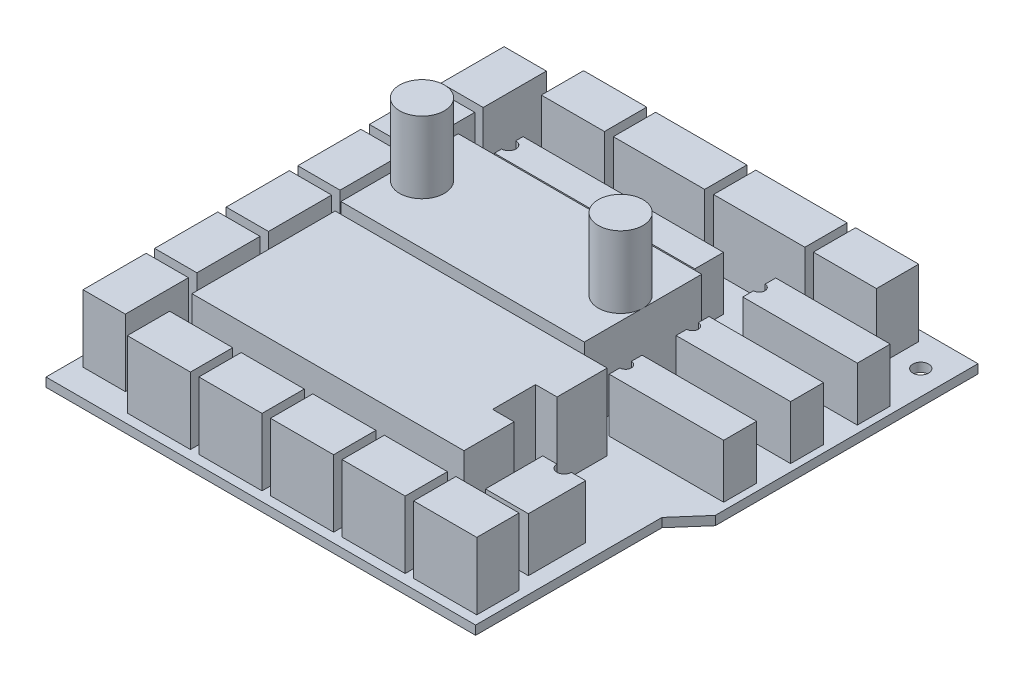
SolidWorks part; units mm, degrees
ref_plane "Front Plane" through (0, 0, 0) normal (0, 0, 1) x (1, 0, 0)
ref_plane "Top Plane" through (0, 0, 0) normal (0, 1, 0) x (1, 0, 0)
ref_plane "Right Plane" through (0, 0, 0) normal (1, 0, 0) x (0, 0, -1)
sketch "Sketch1" plane through (0, 0, 0) normal (0, 1, 0) x (1, 0, 0)
  line L0 (0.0381, 84.724) -> (0.0381, 0)
  line L1 (0.0381, 0) -> (76.2582, 0)
  line L2 (76.2582, 0) -> (76.2582, 33.0707)
  line L3 (76.2582, 33.0707) -> (80.6676, 38.11)
  line L4 (80.6676, 38.11) -> (80.6676, 84.724)
  line L5 (80.6676, 84.724) -> (0.0381, 84.724)
  line L6 (72.0228, 75.3526) -> (60.8228, 75.3526)
  line L7 (60.8228, 75.3526) -> (60.8228, 81.8526)
  line L8 (60.8228, 81.8526) -> (60.8228, 82.8526)
  line L9 (60.8228, 82.8526) -> (72.0228, 82.8526)
  line L10 (72.0228, 82.8526) -> (72.0228, 81.8526)
  line L11 (72.0228, 81.8526) -> (72.0228, 75.3526)
  line L12 (60.8228, 81.8526) -> (72.0228, 81.8526)
  line L13 (14.9428, 65.918) -> (14.9428, 64.648)
  line L14 (50.5027, 64.648) -> (50.5027, 69.728)
  line L15 (14.9428, 69.728) -> (14.9428, 68.458)
  line L16 (14.9428, 69.728) -> (50.5027, 69.728)
  line L17 (15.0698, 64.648) -> (50.5027, 64.648)
  line L18 (16.2128, 62.7684) -> (16.2128, 63.9876)
  line L19 (18.7528, 62.7684) -> (18.7528, 63.9876)
  line L20 (21.2928, 62.7684) -> (21.2928, 63.9876)
  line L21 (23.8328, 62.7684) -> (23.8328, 63.9876)
  line L22 (26.3727, 62.7684) -> (26.3727, 63.9876)
  line L23 (28.9127, 62.7684) -> (28.9127, 63.9876)
  line L24 (31.4527, 62.7684) -> (31.4527, 63.9876)
  line L25 (33.9927, 62.7684) -> (33.9927, 63.9876)
  line L26 (36.5327, 62.7684) -> (36.5327, 63.9876)
  line L27 (39.0727, 62.7684) -> (39.0727, 63.9876)
  line L28 (41.6127, 62.7684) -> (41.6127, 63.9876)
  line L29 (44.1527, 62.7684) -> (44.1527, 63.9876)
  line L30 (46.6927, 62.7684) -> (46.6927, 63.9876)
  line L31 (49.2327, 62.7684) -> (49.2327, 63.9876)
  line L32 (49.2327, 70.3884) -> (49.2327, 71.6076)
  line L33 (46.6927, 70.3884) -> (46.6927, 71.6076)
  line L34 (44.1527, 70.3884) -> (44.1527, 71.6076)
  line L35 (41.6127, 70.3884) -> (41.6127, 71.6076)
  line L36 (39.0727, 70.3884) -> (39.0727, 71.6076)
  line L37 (36.5327, 70.3884) -> (36.5327, 71.6076)
  line L38 (33.9927, 70.3884) -> (33.9927, 71.6076)
  line L39 (31.4527, 70.3884) -> (31.4527, 71.6076)
  line L40 (28.9127, 70.3884) -> (28.9127, 71.6076)
  line L41 (26.3727, 70.3884) -> (26.3727, 71.6076)
  line L42 (23.8328, 70.3884) -> (23.8328, 71.6076)
  line L43 (21.2928, 70.3884) -> (21.2928, 71.6076)
  line L44 (18.7528, 70.3884) -> (18.7528, 71.6076)
  line L45 (16.2128, 70.3884) -> (16.2128, 71.6076)
  line L46 (72.0927, 36.7791) -> (72.0927, 35.2551)
  line L47 (71.8387, 35.0011) -> (71.4577, 35.0011)
  line L48 (71.3307, 35.1281) -> (71.4577, 35.0011)
  line L49 (71.8387, 37.0331) -> (71.4577, 37.0331)
  line L50 (71.3307, 36.9061) -> (71.4577, 37.0331)
  line L51 (67.7747, 35.1281) -> (67.6477, 35.0011)
  line L52 (67.7747, 35.1281) -> (71.3307, 35.1281)
  line L53 (67.7747, 36.9061) -> (67.6477, 37.0331)
  line L54 (67.7747, 36.9061) -> (71.3307, 36.9061)
  line L55 (67.2667, 35.0011) -> (67.6477, 35.0011)
  line L56 (67.2667, 37.0331) -> (67.6477, 37.0331)
  line L57 (67.0127, 36.7791) -> (67.0127, 35.2551)
  line L58 (73.6675, 36.1434) -> (73.6675, 35.8908)
  line L59 (73.6675, 35.8908) -> (73.489, 35.7123)
  line L60 (73.489, 35.7123) -> (73.2363, 35.7123)
  line L61 (73.2363, 35.7123) -> (73.0579, 35.8908)
  line L62 (73.0579, 35.8908) -> (73.0579, 36.1434)
  line L63 (73.0579, 36.1434) -> (73.2363, 36.3219)
  line L64 (73.2363, 36.3219) -> (73.489, 36.3219)
  line L65 (73.489, 36.3219) -> (73.6675, 36.1434)
  line L66 (73.6675, 36.1434) -> (73.6675, 35.8908)
  line L67 (66.0475, 36.1434) -> (66.0475, 35.8908)
  line L68 (66.0475, 35.8908) -> (65.869, 35.7123)
  line L69 (65.869, 35.7123) -> (65.6164, 35.7123)
  line L70 (65.6164, 35.7123) -> (65.4379, 35.8908)
  line L71 (65.4379, 35.8908) -> (65.4379, 36.1434)
  line L72 (65.4379, 36.1434) -> (65.6164, 36.3219)
  line L73 (65.6164, 36.3219) -> (65.869, 36.3219)
  line L74 (65.869, 36.3219) -> (66.0475, 36.1434)
  line L75 (66.0475, 36.1434) -> (66.0475, 35.8908)
  line L76 (72.0927, 32.9691) -> (72.0927, 31.4451)
  line L77 (71.8387, 31.1911) -> (71.4577, 31.1911)
  line L78 (71.3307, 31.3181) -> (71.4577, 31.1911)
  line L79 (71.8387, 33.2231) -> (71.4577, 33.2231)
  line L80 (71.3307, 33.0961) -> (71.4577, 33.2231)
  line L81 (67.7747, 31.3181) -> (67.6477, 31.1911)
  line L82 (67.7747, 31.3181) -> (71.3307, 31.3181)
  line L83 (67.7747, 33.0961) -> (67.6477, 33.2231)
  line L84 (67.7747, 33.0961) -> (71.3307, 33.0961)
  line L85 (67.2667, 31.1911) -> (67.6477, 31.1911)
  line L86 (67.2667, 33.2231) -> (67.6477, 33.2231)
  line L87 (67.0127, 32.9691) -> (67.0127, 31.4451)
  line L88 (73.6675, 32.3334) -> (73.6675, 32.0808)
  line L89 (73.6675, 32.0808) -> (73.489, 31.9023)
  line L90 (73.489, 31.9023) -> (73.2363, 31.9023)
  line L91 (73.2363, 31.9023) -> (73.0579, 32.0808)
  line L92 (73.0579, 32.0808) -> (73.0579, 32.3334)
  line L93 (73.0579, 32.3334) -> (73.2363, 32.5119)
  line L94 (73.2363, 32.5119) -> (73.489, 32.5119)
  line L95 (73.489, 32.5119) -> (73.6675, 32.3334)
  line L96 (73.6675, 32.3334) -> (73.6675, 32.0808)
  line L97 (66.0475, 32.3334) -> (66.0475, 32.0808)
  line L98 (66.0475, 32.0808) -> (65.869, 31.9023)
  line L99 (65.869, 31.9023) -> (65.6164, 31.9023)
  line L100 (65.6164, 31.9023) -> (65.4379, 32.0808)
  line L101 (65.4379, 32.0808) -> (65.4379, 32.3334)
  line L102 (65.4379, 32.3334) -> (65.6164, 32.5119)
  line L103 (65.6164, 32.5119) -> (65.869, 32.5119)
  line L104 (65.869, 32.5119) -> (66.0475, 32.3334)
  line L105 (66.0475, 32.3334) -> (66.0475, 32.0808)
  line L106 (67.0127, 27.6351) -> (67.0127, 29.1591)
  line L107 (67.2667, 29.4131) -> (67.6477, 29.4131)
  line L108 (67.7747, 29.2861) -> (67.6477, 29.4131)
  line L109 (67.2667, 27.3811) -> (67.6477, 27.3811)
  line L110 (67.7747, 27.5081) -> (67.6477, 27.3811)
  line L111 (71.3307, 29.2861) -> (71.4577, 29.4131)
  line L112 (71.3307, 29.2861) -> (67.7747, 29.2861)
  line L113 (71.3307, 27.5081) -> (71.4577, 27.3811)
  line L114 (71.3307, 27.5081) -> (67.7747, 27.5081)
  line L115 (71.8387, 29.4131) -> (71.4577, 29.4131)
  line L116 (71.8387, 27.3811) -> (71.4577, 27.3811)
  line L117 (72.0927, 27.6351) -> (72.0927, 29.1591)
  line L118 (65.4379, 28.2708) -> (65.4379, 28.5235)
  line L119 (65.4379, 28.5235) -> (65.6164, 28.7019)
  line L120 (65.6164, 28.7019) -> (65.869, 28.7019)
  line L121 (65.869, 28.7019) -> (66.0475, 28.5235)
  line L122 (66.0475, 28.5235) -> (66.0475, 28.2708)
  line L123 (66.0475, 28.2708) -> (65.869, 28.0923)
  line L124 (65.869, 28.0923) -> (65.6164, 28.0923)
  line L125 (65.6164, 28.0923) -> (65.4379, 28.2708)
  line L126 (65.4379, 28.2708) -> (65.4379, 28.5235)
  line L127 (73.0579, 28.2708) -> (73.0579, 28.5235)
  line L128 (73.0579, 28.5235) -> (73.2363, 28.7019)
  line L129 (73.2363, 28.7019) -> (73.489, 28.7019)
  line L130 (73.489, 28.7019) -> (73.6675, 28.5235)
  line L131 (73.6675, 28.5235) -> (73.6675, 28.2708)
  line L132 (73.6675, 28.2708) -> (73.489, 28.0923)
  line L133 (73.489, 28.0923) -> (73.2363, 28.0923)
  line L134 (73.2363, 28.0923) -> (73.0579, 28.2708)
  line L135 (73.0579, 28.2708) -> (73.0579, 28.5235)
  line L136 (72.0927, 25.3491) -> (72.0927, 23.8252)
  line L137 (71.8387, 23.5712) -> (71.4577, 23.5712)
  line L138 (71.3307, 23.6982) -> (71.4577, 23.5712)
  line L139 (71.8387, 25.6031) -> (71.4577, 25.6031)
  line L140 (71.3307, 25.4761) -> (71.4577, 25.6031)
  line L141 (67.7747, 23.6982) -> (67.6477, 23.5712)
  line L142 (67.7747, 23.6982) -> (71.3307, 23.6982)
  line L143 (67.7747, 25.4761) -> (67.6477, 25.6031)
  line L144 (67.7747, 25.4761) -> (71.3307, 25.4761)
  line L145 (67.2667, 23.5712) -> (67.6477, 23.5712)
  line L146 (67.2667, 25.6031) -> (67.6477, 25.6031)
  line L147 (67.0127, 25.3491) -> (67.0127, 23.8252)
  line L148 (73.6675, 24.7135) -> (73.6675, 24.4608)
  line L149 (73.6675, 24.4608) -> (73.489, 24.2824)
  line L150 (73.489, 24.2824) -> (73.2363, 24.2824)
  line L151 (73.2363, 24.2824) -> (73.0579, 24.4608)
  line L152 (73.0579, 24.4608) -> (73.0579, 24.7135)
  line L153 (73.0579, 24.7135) -> (73.2363, 24.892)
  line L154 (73.2363, 24.892) -> (73.489, 24.892)
  line L155 (73.489, 24.892) -> (73.6675, 24.7135)
  line L156 (73.6675, 24.7135) -> (73.6675, 24.4608)
  line L157 (66.0475, 24.7135) -> (66.0475, 24.4608)
  line L158 (66.0475, 24.4608) -> (65.869, 24.2824)
  line L159 (65.869, 24.2824) -> (65.6164, 24.2824)
  line L160 (65.6164, 24.2824) -> (65.4379, 24.4608)
  line L161 (65.4379, 24.4608) -> (65.4379, 24.7135)
  line L162 (65.4379, 24.7135) -> (65.6164, 24.892)
  line L163 (65.6164, 24.892) -> (65.869, 24.892)
  line L164 (65.869, 24.892) -> (66.0475, 24.7135)
  line L165 (66.0475, 24.7135) -> (66.0475, 24.4608)
  line L166 (38.2497, 28.8086) -> (39.7737, 28.8086)
  line L167 (40.0277, 28.5546) -> (40.0277, 28.1736)
  line L168 (39.9007, 28.0466) -> (40.0277, 28.1736)
  line L169 (37.9957, 28.5546) -> (37.9957, 28.1736)
  line L170 (38.1227, 28.0466) -> (37.9957, 28.1736)
  line L171 (39.9007, 24.4907) -> (40.0277, 24.3637)
  line L172 (39.9007, 24.4907) -> (39.9007, 28.0466)
  line L173 (38.1227, 24.4907) -> (37.9957, 24.3637)
  line L174 (38.1227, 24.4907) -> (38.1227, 28.0466)
  line L175 (40.0277, 23.9827) -> (40.0277, 24.3637)
  line L176 (37.9957, 23.9827) -> (37.9957, 24.3637)
  line L177 (38.2497, 23.7287) -> (39.7737, 23.7287)
  line L178 (38.8854, 30.3834) -> (39.138, 30.3834)
  line L179 (39.138, 30.3834) -> (39.3165, 30.2049)
  line L180 (39.3165, 30.2049) -> (39.3165, 29.9523)
  line L181 (39.3165, 29.9523) -> (39.138, 29.7738)
  line L182 (39.138, 29.7738) -> (38.8854, 29.7738)
  line L183 (38.8854, 29.7738) -> (38.7069, 29.9523)
  line L184 (38.7069, 29.9523) -> (38.7069, 30.2049)
  line L185 (38.7069, 30.2049) -> (38.8854, 30.3834)
  line L186 (38.8854, 30.3834) -> (39.138, 30.3834)
  line L187 (38.8854, 22.7635) -> (39.138, 22.7635)
  line L188 (39.138, 22.7635) -> (39.3165, 22.585)
  line L189 (39.3165, 22.585) -> (39.3165, 22.3323)
  line L190 (39.3165, 22.3323) -> (39.138, 22.1539)
  line L191 (39.138, 22.1539) -> (38.8854, 22.1539)
  line L192 (38.8854, 22.1539) -> (38.7069, 22.3323)
  line L193 (38.7069, 22.3323) -> (38.7069, 22.585)
  line L194 (38.7069, 22.585) -> (38.8854, 22.7635)
  line L195 (38.8854, 22.7635) -> (39.138, 22.7635)
  line L196 (45.5649, 21.5697) -> (44.0409, 21.5697)
  line L197 (43.7869, 21.8237) -> (43.7869, 22.2047)
  line L198 (43.9139, 22.3317) -> (43.7869, 22.2047)
  line L199 (45.8189, 21.8237) -> (45.8189, 22.2047)
  line L200 (45.6919, 22.3317) -> (45.8189, 22.2047)
  line L201 (43.9139, 25.8876) -> (43.7869, 26.0146)
  line L202 (43.9139, 25.8876) -> (43.9139, 22.3317)
  line L203 (45.6919, 25.8876) -> (45.8189, 26.0146)
  line L204 (45.6919, 25.8876) -> (45.6919, 22.3317)
  line L205 (43.7869, 26.3956) -> (43.7869, 26.0146)
  line L206 (45.8189, 26.3956) -> (45.8189, 26.0146)
  line L207 (45.5649, 26.6496) -> (44.0409, 26.6496)
  line L208 (44.9292, 19.9949) -> (44.6766, 19.9949)
  line L209 (44.6766, 19.9949) -> (44.4981, 20.1734)
  line L210 (44.4981, 20.1734) -> (44.4981, 20.426)
  line L211 (44.4981, 20.426) -> (44.6766, 20.6045)
  line L212 (44.6766, 20.6045) -> (44.9292, 20.6045)
  line L213 (44.9292, 20.6045) -> (45.1077, 20.426)
  line L214 (45.1077, 20.426) -> (45.1077, 20.1734)
  line L215 (45.1077, 20.1734) -> (44.9292, 19.9949)
  line L216 (44.9292, 19.9949) -> (44.6766, 19.9949)
  line L217 (44.9292, 27.6148) -> (44.6766, 27.6148)
  line L218 (44.6766, 27.6148) -> (44.4981, 27.7933)
  line L219 (44.4981, 27.7933) -> (44.4981, 28.046)
  line L220 (44.4981, 28.046) -> (44.6766, 28.2244)
  line L221 (44.6766, 28.2244) -> (44.9292, 28.2244)
  line L222 (44.9292, 28.2244) -> (45.1077, 28.046)
  line L223 (45.1077, 28.046) -> (45.1077, 27.7933)
  line L224 (45.1077, 27.7933) -> (44.9292, 27.6148)
  line L225 (44.9292, 27.6148) -> (44.6766, 27.6148)
  line L226 (54.3229, 65.156) -> (52.7989, 65.156)
  line L227 (52.5449, 65.41) -> (52.5449, 65.791)
  line L228 (52.6719, 65.918) -> (52.5449, 65.791)
  line L229 (54.5769, 65.41) -> (54.5769, 65.791)
  line L230 (54.4499, 65.918) -> (54.5769, 65.791)
  line L231 (52.6719, 69.474) -> (52.5449, 69.601)
  line L232 (52.6719, 69.474) -> (52.6719, 65.918)
  line L233 (54.4499, 69.474) -> (54.5769, 69.601)
  line L234 (54.4499, 69.474) -> (54.4499, 65.918)
  line L235 (52.5449, 69.982) -> (52.5449, 69.601)
  line L236 (54.5769, 69.982) -> (54.5769, 69.601)
  line L237 (54.3229, 70.236) -> (52.7989, 70.236)
  line L238 (53.6872, 63.5812) -> (53.4346, 63.5812)
  line L239 (53.4346, 63.5812) -> (53.2561, 63.7597)
  line L240 (53.2561, 63.7597) -> (53.2561, 64.0123)
  line L241 (53.2561, 64.0123) -> (53.4346, 64.1908)
  line L242 (53.4346, 64.1908) -> (53.6872, 64.1908)
  line L243 (53.6872, 64.1908) -> (53.8657, 64.0123)
  line L244 (53.8657, 64.0123) -> (53.8657, 63.7597)
  line L245 (53.8657, 63.7597) -> (53.6872, 63.5812)
  line L246 (53.6872, 63.5812) -> (53.4346, 63.5812)
  line L247 (53.6872, 71.2012) -> (53.4346, 71.2012)
  line L248 (53.4346, 71.2012) -> (53.2561, 71.3796)
  line L249 (53.2561, 71.3796) -> (53.2561, 71.6323)
  line L250 (53.2561, 71.6323) -> (53.4346, 71.8108)
  line L251 (53.4346, 71.8108) -> (53.6872, 71.8108)
  line L252 (53.6872, 71.8108) -> (53.8657, 71.6323)
  line L253 (53.8657, 71.6323) -> (53.8657, 71.3796)
  line L254 (53.8657, 71.3796) -> (53.6872, 71.2012)
  line L255 (53.6872, 71.2012) -> (53.4346, 71.2012)
  line L256 (61.9327, 12.2631) -> (13.6728, 12.2631)
  line L257 (61.9327, 12.2631) -> (61.9327, 21.1531)
  line L258 (61.9327, 21.1531) -> (61.9327, 28.773)
  line L259 (61.9327, 28.773) -> (61.9327, 37.663)
  line L260 (13.6728, 12.2631) -> (13.6728, 17.3431)
  line L261 (13.6728, 17.3431) -> (13.6728, 32.583)
  line L262 (13.6728, 32.583) -> (13.6728, 37.663)
  line L263 (13.6728, 37.663) -> (61.9327, 37.663)
  line L264 (13.6728, 17.3431) -> (36.5327, 17.3431)
  line L265 (36.5327, 17.3431) -> (36.5327, 32.583)
  line L266 (36.5327, 32.583) -> (13.6728, 32.583)
  line L267 (61.9327, 21.1531) -> (58.1227, 21.1531)
  line L268 (58.1227, 21.1531) -> (58.1227, 28.773)
  line L269 (58.1227, 28.773) -> (61.9327, 28.773)
  line L270 (18.7528, 19.8831) -> (14.9428, 19.8831)
  line L271 (14.9428, 19.8831) -> (14.9428, 21.1531)
  line L272 (14.9428, 21.1531) -> (17.4828, 21.1531)
  line L273 (17.4828, 21.1531) -> (17.4828, 22.4231)
  line L274 (17.4828, 22.4231) -> (14.9428, 22.4231)
  line L275 (14.9428, 22.4231) -> (14.9428, 23.6931)
  line L276 (14.9428, 23.6931) -> (17.4828, 23.6931)
  line L277 (17.4828, 23.6931) -> (17.4828, 24.9631)
  line L278 (17.4828, 24.9631) -> (14.9428, 24.9631)
  line L279 (14.9428, 24.9631) -> (14.9428, 26.233)
  line L280 (14.9428, 26.233) -> (17.4828, 26.233)
  line L281 (17.4828, 26.233) -> (17.4828, 27.503)
  line L282 (17.4828, 27.503) -> (14.9428, 27.503)
  line L283 (14.9428, 27.503) -> (14.9428, 30.043)
  line L284 (58.1227, 17.3431) -> (58.1227, 19.8831)
  line L285 (58.1227, 19.8831) -> (60.6627, 19.8831)
  line L286 (60.6627, 19.8831) -> (60.6627, 17.3431)
  line L287 (60.6627, 17.3431) -> (58.1227, 17.3431)
  line L288 (58.1227, 30.043) -> (60.6627, 30.043)
  line L289 (60.6627, 30.043) -> (60.6627, 32.583)
  line L290 (60.6627, 32.583) -> (58.1227, 32.583)
  line L291 (58.1227, 32.583) -> (58.1227, 30.043)
  line L292 (55.9078, 39.634) -> (12.7279, 39.634)
  line L293 (12.7279, 39.634) -> (12.7279, 60.462)
  line L294 (12.7279, 60.462) -> (55.9078, 60.462)
  line L295 (55.9078, 60.462) -> (55.9078, 39.634)
  line L296 (14.6329, 43.063) -> (14.6329, 44.333)
  line L297 (15.2679, 43.698) -> (13.9979, 43.698)
  line L298 (54.0028, 57.033) -> (54.0028, 55.763)
  line L299 (14.6329, 57.033) -> (14.6329, 55.763)
  line L300 (54.0028, 43.063) -> (54.0028, 44.333)
  line L301 (54.6378, 43.698) -> (53.3678, 43.698)
  line L302 (53.19, 49.2613) -> (54.8156, 49.2613)
  line L303 (54.8156, 49.0807) -> (54.8156, 49.4419)
  line L304 (53.19, 49.0807) -> (53.19, 49.4419)
  line L305 (54.8156, 50.1123) -> (53.19, 50.1123)
  line L306 (53.19, 50.1123) -> (54.8156, 51.0154)
  line L307 (54.8156, 51.0154) -> (53.19, 51.0154)
  line L308 (14.9942, 48.0334) -> (14.2717, 48.0334)
  line L309 (14.2717, 48.9365) -> (14.9942, 48.9365)
  line L310 (13.8201, 49.6486) -> (14.9942, 49.6486)
  line L311 (14.9942, 50.5517) -> (13.8201, 50.5517)
  line L312 (15.4457, 51.6112) -> (13.8201, 51.6112)
  line L313 (13.8201, 51.1596) -> (13.8201, 52.0627)
  line L314 (73.3627, 22.4231) -> (73.3627, 12.2631)
  line L315 (73.3627, 12.2631) -> (65.7427, 12.2631)
  line L316 (65.7427, 12.2631) -> (65.7427, 22.4231)
  line L317 (65.7427, 22.4231) -> (68.2827, 22.4231)
  line L318 (70.8227, 22.4231) -> (73.3627, 22.4231)
  line L319 (64.9934, 21.1531) -> (66.492, 21.1531)
  line L320 (64.9934, 18.6131) -> (66.492, 18.6131)
  line L321 (64.9934, 16.0731) -> (66.492, 16.0731)
  line L322 (64.9934, 13.5331) -> (66.492, 13.5331)
  line L323 (72.6134, 13.5331) -> (74.112, 13.5331)
  line L324 (72.6134, 16.0731) -> (74.112, 16.0731)
  line L325 (72.6134, 18.6131) -> (74.112, 18.6131)
  line L326 (72.6134, 21.1531) -> (74.112, 21.1531)
  line L327 (63.5977, 9.1682) -> (74.7977, 9.1682)
  line L328 (74.7977, 9.1682) -> (74.7977, 2.6682)
  line L329 (74.7977, 2.6682) -> (74.7977, 1.6682)
  line L330 (74.7977, 1.6682) -> (63.5977, 1.6682)
  line L331 (63.5977, 1.6682) -> (63.5977, 2.6682)
  line L332 (63.5977, 2.6682) -> (63.5977, 9.1682)
  line L333 (74.7977, 2.6682) -> (63.5977, 2.6682)
  line L334 (79.3976, 46.7105) -> (59.0777, 46.7105)
  line L335 (59.0777, 40.8685) -> (79.3976, 40.8685)
  line L336 (79.3976, 46.7105) -> (79.3976, 40.8685)
  line L337 (59.0777, 46.7105) -> (59.0777, 44.8055)
  line L338 (59.0777, 40.8685) -> (59.0777, 42.7735)
  line L339 (60.3477, 39.3699) -> (60.3477, 40.5891)
  line L340 (62.8877, 39.3699) -> (62.8877, 40.5891)
  line L341 (65.4277, 39.3699) -> (65.4277, 40.5891)
  line L342 (67.9677, 39.3699) -> (67.9677, 40.5891)
  line L343 (70.5077, 39.3699) -> (70.5077, 40.5891)
  line L344 (73.0477, 39.3699) -> (73.0477, 40.5891)
  line L345 (75.5876, 39.3699) -> (75.5876, 40.5891)
  line L346 (78.1276, 39.3699) -> (78.1276, 40.5891)
  line L347 (78.1276, 46.9899) -> (78.1276, 48.2091)
  line L348 (75.5876, 46.9899) -> (75.5876, 48.2091)
  line L349 (73.0477, 46.9899) -> (73.0477, 48.2091)
  line L350 (70.5077, 46.9899) -> (70.5077, 48.2091)
  line L351 (67.9677, 46.9899) -> (67.9677, 48.2091)
  line L352 (65.4277, 46.9899) -> (65.4277, 48.2091)
  line L353 (62.8877, 46.9899) -> (62.8877, 48.2091)
  line L354 (60.3477, 46.9899) -> (60.3477, 48.2091)
  line L355 (50.8977, 9.1682) -> (62.0977, 9.1682)
  line L356 (62.0977, 9.1682) -> (62.0977, 2.6682)
  line L357 (62.0977, 2.6682) -> (62.0977, 1.6682)
  line L358 (62.0977, 1.6682) -> (50.8977, 1.6682)
  line L359 (50.8977, 1.6682) -> (50.8977, 2.6682)
  line L360 (50.8977, 2.6682) -> (50.8977, 9.1682)
  line L361 (62.0977, 2.6682) -> (50.8977, 2.6682)
  line L362 (38.1977, 9.1682) -> (49.3977, 9.1682)
  line L363 (49.3977, 9.1682) -> (49.3977, 2.6682)
  line L364 (49.3977, 2.6682) -> (49.3977, 1.6682)
  line L365 (49.3977, 1.6682) -> (38.1977, 1.6682)
  line L366 (38.1977, 1.6682) -> (38.1977, 2.6682)
  line L367 (38.1977, 2.6682) -> (38.1977, 9.1682)
  line L368 (49.3977, 2.6682) -> (38.1977, 2.6682)
  line L369 (25.4977, 9.1682) -> (36.6977, 9.1682)
  line L370 (36.6977, 9.1682) -> (36.6977, 2.6682)
  line L371 (36.6977, 2.6682) -> (36.6977, 1.6682)
  line L372 (36.6977, 1.6682) -> (25.4977, 1.6682)
  line L373 (25.4977, 1.6682) -> (25.4977, 2.6682)
  line L374 (25.4977, 2.6682) -> (25.4977, 9.1682)
  line L375 (36.6977, 2.6682) -> (25.4977, 2.6682)
  line L376 (12.7978, 9.1682) -> (23.9978, 9.1682)
  line L377 (23.9978, 9.1682) -> (23.9978, 2.6682)
  line L378 (23.9978, 2.6682) -> (23.9978, 1.6682)
  line L379 (23.9978, 1.6682) -> (12.7978, 1.6682)
  line L380 (12.7978, 1.6682) -> (12.7978, 2.6682)
  line L381 (12.7978, 2.6682) -> (12.7978, 9.1682)
  line L382 (23.9978, 2.6682) -> (12.7978, 2.6682)
  line L383 (79.3976, 58.5875) -> (59.0777, 58.5875)
  line L384 (59.0777, 52.7455) -> (79.3976, 52.7455)
  line L385 (79.3976, 58.5875) -> (79.3976, 52.7455)
  line L386 (59.0777, 58.5875) -> (59.0777, 56.6825)
  line L387 (59.0777, 52.7455) -> (59.0777, 54.6505)
  line L388 (60.3477, 51.2469) -> (60.3477, 52.4661)
  line L389 (62.8877, 51.2469) -> (62.8877, 52.4661)
  line L390 (65.4277, 51.2469) -> (65.4277, 52.4661)
  line L391 (67.9677, 51.2469) -> (67.9677, 52.4661)
  line L392 (70.5077, 51.2469) -> (70.5077, 52.4661)
  line L393 (73.0477, 51.2469) -> (73.0477, 52.4661)
  line L394 (75.5876, 51.2469) -> (75.5876, 52.4661)
  line L395 (78.1276, 51.2469) -> (78.1276, 52.4661)
  line L396 (78.1276, 58.8669) -> (78.1276, 60.0861)
  line L397 (75.5876, 58.8669) -> (75.5876, 60.0861)
  line L398 (73.0477, 58.8669) -> (73.0477, 60.0861)
  line L399 (70.5077, 58.8669) -> (70.5077, 60.0861)
  line L400 (67.9677, 58.8669) -> (67.9677, 60.0861)
  line L401 (65.4277, 58.8669) -> (65.4277, 60.0861)
  line L402 (62.8877, 58.8669) -> (62.8877, 60.0861)
  line L403 (60.3477, 58.8669) -> (60.3477, 60.0861)
  line L404 (9.3181, 15.993) -> (9.3181, 4.793)
  line L405 (9.3181, 4.793) -> (2.8181, 4.793)
  line L406 (2.8181, 4.793) -> (1.8181, 4.793)
  line L407 (1.8181, 4.793) -> (1.8181, 15.993)
  line L408 (1.8181, 15.993) -> (2.8181, 15.993)
  line L409 (2.8181, 15.993) -> (9.3181, 15.993)
  line L410 (2.8181, 4.793) -> (2.8181, 15.993)
  line L411 (9.3181, 28.6929) -> (9.3181, 17.493)
  line L412 (9.3181, 17.493) -> (2.8181, 17.493)
  line L413 (2.8181, 17.493) -> (1.8181, 17.493)
  line L414 (1.8181, 17.493) -> (1.8181, 28.6929)
  line L415 (1.8181, 28.6929) -> (2.8181, 28.6929)
  line L416 (2.8181, 28.6929) -> (9.3181, 28.6929)
  line L417 (2.8181, 17.493) -> (2.8181, 28.6929)
  line L418 (9.3181, 41.3929) -> (9.3181, 30.1929)
  line L419 (9.3181, 30.1929) -> (2.8181, 30.1929)
  line L420 (2.8181, 30.1929) -> (1.8181, 30.1929)
  line L421 (1.8181, 30.1929) -> (1.8181, 41.3929)
  line L422 (1.8181, 41.3929) -> (2.8181, 41.3929)
  line L423 (2.8181, 41.3929) -> (9.3181, 41.3929)
  line L424 (2.8181, 30.1929) -> (2.8181, 41.3929)
  line L425 (9.3181, 54.0929) -> (9.3181, 42.8929)
  line L426 (9.3181, 42.8929) -> (2.8181, 42.8929)
  line L427 (2.8181, 42.8929) -> (1.8181, 42.8929)
  line L428 (1.8181, 42.8929) -> (1.8181, 54.0929)
  line L429 (1.8181, 54.0929) -> (2.8181, 54.0929)
  line L430 (2.8181, 54.0929) -> (9.3181, 54.0929)
  line L431 (2.8181, 42.8929) -> (2.8181, 54.0929)
  line L432 (79.3976, 70.4239) -> (59.0777, 70.4239)
  line L433 (59.0777, 64.5819) -> (79.3976, 64.5819)
  line L434 (79.3976, 70.4239) -> (79.3976, 64.5819)
  line L435 (59.0777, 70.4239) -> (59.0777, 68.5189)
  line L436 (59.0777, 64.5819) -> (59.0777, 66.4869)
  line L437 (60.3477, 63.0833) -> (60.3477, 64.3025)
  line L438 (62.8877, 63.0833) -> (62.8877, 64.3025)
  line L439 (65.4277, 63.0833) -> (65.4277, 64.3025)
  line L440 (67.9677, 63.0833) -> (67.9677, 64.3025)
  line L441 (70.5077, 63.0833) -> (70.5077, 64.3025)
  line L442 (73.0477, 63.0833) -> (73.0477, 64.3025)
  line L443 (75.5876, 63.0833) -> (75.5876, 64.3025)
  line L444 (78.1276, 63.0833) -> (78.1276, 64.3025)
  line L445 (78.1276, 70.7033) -> (78.1276, 71.9225)
  line L446 (75.5876, 70.7033) -> (75.5876, 71.9225)
  line L447 (73.0477, 70.7033) -> (73.0477, 71.9225)
  line L448 (70.5077, 70.7033) -> (70.5077, 71.9225)
  line L449 (67.9677, 70.7033) -> (67.9677, 71.9225)
  line L450 (65.4277, 70.7033) -> (65.4277, 71.9225)
  line L451 (62.8877, 70.7033) -> (62.8877, 71.9225)
  line L452 (60.3477, 70.7033) -> (60.3477, 71.9225)
  line L453 (9.3181, 66.7929) -> (9.3181, 55.5929)
  line L454 (9.3181, 55.5929) -> (2.8181, 55.5929)
  line L455 (2.8181, 55.5929) -> (1.8181, 55.5929)
  line L456 (1.8181, 55.5929) -> (1.8181, 66.7929)
  line L457 (1.8181, 66.7929) -> (2.8181, 66.7929)
  line L458 (2.8181, 66.7929) -> (9.3181, 66.7929)
  line L459 (2.8181, 55.5929) -> (2.8181, 66.7929)
  line L460 (9.3181, 79.4928) -> (9.3181, 68.2929)
  line L461 (9.3181, 68.2929) -> (2.8181, 68.2929)
  line L462 (2.8181, 68.2929) -> (1.8181, 68.2929)
  line L463 (1.8181, 68.2929) -> (1.8181, 79.4928)
  line L464 (1.8181, 79.4928) -> (2.8181, 79.4928)
  line L465 (2.8181, 79.4928) -> (9.3181, 79.4928)
  line L466 (2.8181, 68.2929) -> (2.8181, 79.4928)
  line L467 (23.7629, 75.3526) -> (12.5629, 75.3526)
  line L468 (12.5629, 75.3526) -> (12.5629, 81.8526)
  line L469 (12.5629, 81.8526) -> (12.5629, 82.8526)
  line L470 (12.5629, 82.8526) -> (23.7629, 82.8526)
  line L471 (23.7629, 82.8526) -> (23.7629, 81.8526)
  line L472 (23.7629, 81.8526) -> (23.7629, 75.3526)
  line L473 (12.5629, 81.8526) -> (23.7629, 81.8526)
  line L474 (41.5428, 75.3526) -> (25.3428, 75.3526)
  line L475 (25.3428, 75.3526) -> (25.3428, 81.8526)
  line L476 (25.3428, 81.8526) -> (25.3428, 82.8526)
  line L477 (25.3428, 82.8526) -> (41.5428, 82.8526)
  line L478 (41.5428, 82.8526) -> (41.5428, 81.8526)
  line L479 (41.5428, 81.8526) -> (41.5428, 75.3526)
  line L480 (25.3428, 81.8526) -> (41.5428, 81.8526)
  line L481 (59.3228, 75.3526) -> (43.1228, 75.3526)
  line L482 (43.1228, 75.3526) -> (43.1228, 81.8526)
  line L483 (43.1228, 81.8526) -> (43.1228, 82.8526)
  line L484 (43.1228, 82.8526) -> (59.3228, 82.8526)
  line L485 (59.3228, 82.8526) -> (59.3228, 81.8526)
  line L486 (59.3228, 81.8526) -> (59.3228, 75.3526)
  line L487 (43.1228, 81.8526) -> (59.3228, 81.8526)
  arc A0 (0, 0) -> (0.0762, 0) centre (0.0381, 0) ccw
  arc A1 (0.0762, 84.724) -> (0, 84.724) centre (0.0381, 84.724) ccw
  arc A2 (76.2582, -0.0381) -> (76.2582, 0.0381) centre (76.2582, 0) ccw
  arc A3 (0.0381, 0.0381) -> (0.0381, -0.0381) centre (0.0381, 0) ccw
  arc A4 (76.2963, 33.0707) -> (76.2201, 33.0707) centre (76.2582, 33.0707) ccw
  arc A5 (76.2201, 0) -> (76.2963, 0) centre (76.2582, 0) ccw
  arc A6 (80.6963, 38.085) -> (80.639, 38.1351) centre (80.6677, 38.1101) ccw
  arc A7 (76.2295, 33.0958) -> (76.2869, 33.0456) centre (76.2582, 33.0707) ccw
  arc A8 (80.7057, 84.724) -> (80.6295, 84.724) centre (80.6676, 84.724) ccw
  arc A9 (80.6295, 38.11) -> (80.7057, 38.11) centre (80.6676, 38.11) ccw
  arc A10 (0.0381, 84.7621) -> (0.0381, 84.6859) centre (0.0381, 84.724) ccw
  arc A11 (80.6676, 84.6859) -> (80.6676, 84.7621) centre (80.6676, 84.724) ccw
  arc A12 (60.8228, 75.4034) -> (60.8228, 75.3018) centre (60.8228, 75.3526) ccw
  arc A13 (72.0228, 75.3018) -> (72.0228, 75.4034) centre (72.0228, 75.3526) ccw
  arc A14 (60.8736, 81.8526) -> (60.772, 81.8526) centre (60.8228, 81.8526) ccw
  arc A15 (60.772, 75.3526) -> (60.8736, 75.3526) centre (60.8228, 75.3526) ccw
  arc A16 (60.8736, 82.8526) -> (60.772, 82.8526) centre (60.8228, 82.8526) ccw
  arc A17 (60.772, 81.8526) -> (60.8736, 81.8526) centre (60.8228, 81.8526) ccw
  arc A18 (72.0228, 82.8018) -> (72.0228, 82.9034) centre (72.0228, 82.8526) ccw
  arc A19 (60.8228, 82.9034) -> (60.8228, 82.8018) centre (60.8228, 82.8526) ccw
  arc A20 (71.972, 81.8526) -> (72.0736, 81.8526) centre (72.0228, 81.8526) ccw
  arc A21 (72.0736, 82.8526) -> (71.972, 82.8526) centre (72.0228, 82.8526) ccw
  arc A22 (71.972, 75.3526) -> (72.0736, 75.3526) centre (72.0228, 75.3526) ccw
  arc A23 (72.0736, 81.8526) -> (71.972, 81.8526) centre (72.0228, 81.8526) ccw
  arc A24 (72.0228, 81.8018) -> (72.0228, 81.9034) centre (72.0228, 81.8526) ccw
  arc A25 (60.8228, 81.9034) -> (60.8228, 81.8018) centre (60.8228, 81.8526) ccw
  circle A26 centre (63.9228, 79.5526) radius 0.508
  circle A27 centre (26.5734, 24.7243) radius 2.921
  circle A28 centre (26.5734, 24.7243) radius 1.5
  circle A29 centre (26.5734, 24.7243) radius 1.4
  circle A30 centre (76.3369, 78.8973) radius 2.921
  circle A31 centre (76.3369, 78.8973) radius 1.5
  circle A32 centre (76.3369, 78.8973) radius 1.4
  arc A33 (14.9047, 64.648) -> (14.9809, 64.648) centre (14.9428, 64.648) ccw
  arc A34 (14.9809, 65.918) -> (14.9047, 65.918) centre (14.9428, 65.918) ccw
  arc A35 (14.9428, 65.918) -> (14.9428, 68.458) centre (14.9428, 67.188) ccw
  arc A36 (14.9428, 65.9561) -> (14.9428, 65.8799) centre (14.9428, 65.918) ccw
  arc A37 (14.9428, 68.4961) -> (14.9428, 68.4199) centre (14.9428, 68.458) ccw
  arc A38 (50.5408, 69.728) -> (50.4646, 69.728) centre (50.5027, 69.728) ccw
  arc A39 (50.4646, 64.648) -> (50.5408, 64.648) centre (50.5027, 64.648) ccw
  arc A40 (14.9047, 68.458) -> (14.9809, 68.458) centre (14.9428, 68.458) ccw
  arc A41 (14.9809, 69.728) -> (14.9047, 69.728) centre (14.9428, 69.728) ccw
  arc A42 (50.5027, 69.6899) -> (50.5027, 69.7661) centre (50.5027, 69.728) ccw
  arc A43 (14.9428, 69.7661) -> (14.9428, 69.6899) centre (14.9428, 69.728) ccw
  arc A44 (50.5027, 64.6099) -> (50.5027, 64.6861) centre (50.5027, 64.648) ccw
  arc A45 (15.0698, 64.6861) -> (15.0698, 64.6099) centre (15.0698, 64.648) ccw
  arc A46 (16.5176, 63.9876) -> (15.908, 63.9876) centre (16.2128, 63.9876) ccw
  arc A47 (15.908, 62.7684) -> (16.5176, 62.7684) centre (16.2128, 62.7684) ccw
  arc A48 (19.0576, 63.9876) -> (18.448, 63.9876) centre (18.7528, 63.9876) ccw
  arc A49 (18.448, 62.7684) -> (19.0576, 62.7684) centre (18.7528, 62.7684) ccw
  arc A50 (21.5976, 63.9876) -> (20.988, 63.9876) centre (21.2928, 63.9876) ccw
  arc A51 (20.988, 62.7684) -> (21.5976, 62.7684) centre (21.2928, 62.7684) ccw
  arc A52 (24.1376, 63.9876) -> (23.528, 63.9876) centre (23.8328, 63.9876) ccw
  arc A53 (23.528, 62.7684) -> (24.1376, 62.7684) centre (23.8328, 62.7684) ccw
  arc A54 (26.6775, 63.9876) -> (26.0679, 63.9876) centre (26.3727, 63.9876) ccw
  arc A55 (26.0679, 62.7684) -> (26.6775, 62.7684) centre (26.3727, 62.7684) ccw
  arc A56 (29.2175, 63.9876) -> (28.6079, 63.9876) centre (28.9127, 63.9876) ccw
  arc A57 (28.6079, 62.7684) -> (29.2175, 62.7684) centre (28.9127, 62.7684) ccw
  arc A58 (31.7575, 63.9876) -> (31.1479, 63.9876) centre (31.4527, 63.9876) ccw
  arc A59 (31.1479, 62.7684) -> (31.7575, 62.7684) centre (31.4527, 62.7684) ccw
  arc A60 (34.2975, 63.9876) -> (33.6879, 63.9876) centre (33.9927, 63.9876) ccw
  arc A61 (33.6879, 62.7684) -> (34.2975, 62.7684) centre (33.9927, 62.7684) ccw
  arc A62 (36.8375, 63.9876) -> (36.2279, 63.9876) centre (36.5327, 63.9876) ccw
  arc A63 (36.2279, 62.7684) -> (36.8375, 62.7684) centre (36.5327, 62.7684) ccw
  arc A64 (39.3775, 63.9876) -> (38.7679, 63.9876) centre (39.0727, 63.9876) ccw
  arc A65 (38.7679, 62.7684) -> (39.3775, 62.7684) centre (39.0727, 62.7684) ccw
  arc A66 (41.9175, 63.9876) -> (41.3079, 63.9876) centre (41.6127, 63.9876) ccw
  arc A67 (41.3079, 62.7684) -> (41.9175, 62.7684) centre (41.6127, 62.7684) ccw
  arc A68 (44.4575, 63.9876) -> (43.8479, 63.9876) centre (44.1527, 63.9876) ccw
  arc A69 (43.8479, 62.7684) -> (44.4575, 62.7684) centre (44.1527, 62.7684) ccw
  arc A70 (46.9975, 63.9876) -> (46.3879, 63.9876) centre (46.6927, 63.9876) ccw
  arc A71 (46.3879, 62.7684) -> (46.9975, 62.7684) centre (46.6927, 62.7684) ccw
  arc A72 (49.5375, 63.9876) -> (48.9279, 63.9876) centre (49.2327, 63.9876) ccw
  arc A73 (48.9279, 62.7684) -> (49.5375, 62.7684) centre (49.2327, 62.7684) ccw
  arc A74 (49.5375, 71.6076) -> (48.9279, 71.6076) centre (49.2327, 71.6076) ccw
  arc A75 (48.9279, 70.3884) -> (49.5375, 70.3884) centre (49.2327, 70.3884) ccw
  arc A76 (46.9975, 71.6076) -> (46.3879, 71.6076) centre (46.6927, 71.6076) ccw
  arc A77 (46.3879, 70.3884) -> (46.9975, 70.3884) centre (46.6927, 70.3884) ccw
  arc A78 (44.4575, 71.6076) -> (43.8479, 71.6076) centre (44.1527, 71.6076) ccw
  arc A79 (43.8479, 70.3884) -> (44.4575, 70.3884) centre (44.1527, 70.3884) ccw
  arc A80 (41.9175, 71.6076) -> (41.3079, 71.6076) centre (41.6127, 71.6076) ccw
  arc A81 (41.3079, 70.3884) -> (41.9175, 70.3884) centre (41.6127, 70.3884) ccw
  arc A82 (39.3775, 71.6076) -> (38.7679, 71.6076) centre (39.0727, 71.6076) ccw
  arc A83 (38.7679, 70.3884) -> (39.3775, 70.3884) centre (39.0727, 70.3884) ccw
  arc A84 (36.8375, 71.6076) -> (36.2279, 71.6076) centre (36.5327, 71.6076) ccw
  arc A85 (36.2279, 70.3884) -> (36.8375, 70.3884) centre (36.5327, 70.3884) ccw
  arc A86 (34.2975, 71.6076) -> (33.6879, 71.6076) centre (33.9927, 71.6076) ccw
  arc A87 (33.6879, 70.3884) -> (34.2975, 70.3884) centre (33.9927, 70.3884) ccw
  arc A88 (31.7575, 71.6076) -> (31.1479, 71.6076) centre (31.4527, 71.6076) ccw
  arc A89 (31.1479, 70.3884) -> (31.7575, 70.3884) centre (31.4527, 70.3884) ccw
  arc A90 (29.2175, 71.6076) -> (28.6079, 71.6076) centre (28.9127, 71.6076) ccw
  arc A91 (28.6079, 70.3884) -> (29.2175, 70.3884) centre (28.9127, 70.3884) ccw
  arc A92 (26.6775, 71.6076) -> (26.0679, 71.6076) centre (26.3727, 71.6076) ccw
  arc A93 (26.0679, 70.3884) -> (26.6775, 70.3884) centre (26.3727, 70.3884) ccw
  arc A94 (24.1376, 71.6076) -> (23.528, 71.6076) centre (23.8328, 71.6076) ccw
  arc A95 (23.528, 70.3884) -> (24.1376, 70.3884) centre (23.8328, 70.3884) ccw
  arc A96 (21.5976, 71.6076) -> (20.988, 71.6076) centre (21.2928, 71.6076) ccw
  arc A97 (20.988, 70.3884) -> (21.5976, 70.3884) centre (21.2928, 70.3884) ccw
  arc A98 (19.0576, 71.6076) -> (18.448, 71.6076) centre (18.7528, 71.6076) ccw
  arc A99 (18.448, 70.3884) -> (19.0576, 70.3884) centre (18.7528, 70.3884) ccw
  arc A100 (16.5176, 71.6076) -> (15.908, 71.6076) centre (16.2128, 71.6076) ccw
  arc A101 (15.908, 70.3884) -> (16.5176, 70.3884) centre (16.2128, 70.3884) ccw
  arc A102 (71.8387, 35.0011) -> (72.0927, 35.2551) centre (71.8387, 35.2551) ccw
  arc A103 (71.8387, 35.0392) -> (71.8387, 34.963) centre (71.8387, 35.0011) ccw
  arc A104 (72.1308, 35.2551) -> (72.0546, 35.2551) centre (72.0927, 35.2551) ccw
  arc A105 (72.0927, 36.7791) -> (71.8387, 37.0331) centre (71.8387, 36.7791) ccw
  arc A106 (72.0546, 36.7791) -> (72.1308, 36.7791) centre (72.0927, 36.7791) ccw
  arc A107 (71.8387, 37.0712) -> (71.8387, 36.995) centre (71.8387, 37.0331) ccw
  arc A108 (67.2667, 37.0331) -> (67.0127, 36.7791) centre (67.2667, 36.7791) ccw
  arc A109 (67.2667, 36.995) -> (67.2667, 37.0712) centre (67.2667, 37.0331) ccw
  arc A110 (66.9746, 36.7791) -> (67.0508, 36.7791) centre (67.0127, 36.7791) ccw
  arc A111 (67.0127, 35.2551) -> (67.2667, 35.0011) centre (67.2667, 35.2551) ccw
  arc A112 (67.0508, 35.2551) -> (66.9746, 35.2551) centre (67.0127, 35.2551) ccw
  arc A113 (67.2667, 34.963) -> (67.2667, 35.0392) centre (67.2667, 35.0011) ccw
  arc A114 (72.0546, 35.2551) -> (72.1308, 35.2551) centre (72.0927, 35.2551) ccw
  arc A115 (72.1308, 36.7791) -> (72.0546, 36.7791) centre (72.0927, 36.7791) ccw
  arc A116 (71.4577, 35.0392) -> (71.4577, 34.963) centre (71.4577, 35.0011) ccw
  arc A117 (71.8387, 34.963) -> (71.8387, 35.0392) centre (71.8387, 35.0011) ccw
  arc A118 (71.4308, 34.9741) -> (71.4846, 35.028) centre (71.4577, 35.0011) ccw
  arc A119 (71.3576, 35.155) -> (71.3038, 35.1011) centre (71.3307, 35.1281) ccw
  arc A120 (71.4577, 37.0712) -> (71.4577, 36.995) centre (71.4577, 37.0331) ccw
  arc A121 (71.8387, 36.995) -> (71.8387, 37.0712) centre (71.8387, 37.0331) ccw
  arc A122 (71.4846, 37.0061) -> (71.4308, 37.06) centre (71.4577, 37.0331) ccw
  arc A123 (71.3038, 36.933) -> (71.3576, 36.8791) centre (71.3307, 36.9061) ccw
  arc A124 (67.6208, 35.028) -> (67.6746, 34.9741) centre (67.6477, 35.0011) ccw
  arc A125 (67.8016, 35.1011) -> (67.7478, 35.155) centre (67.7747, 35.1281) ccw
  arc A126 (71.3307, 35.09) -> (71.3307, 35.1662) centre (71.3307, 35.1281) ccw
  arc A127 (67.7747, 35.1662) -> (67.7747, 35.09) centre (67.7747, 35.1281) ccw
  arc A128 (67.6746, 37.06) -> (67.6208, 37.0061) centre (67.6477, 37.0331) ccw
  arc A129 (67.7478, 36.8791) -> (67.8016, 36.933) centre (67.7747, 36.9061) ccw
  arc A130 (71.3307, 36.868) -> (71.3307, 36.9442) centre (71.3307, 36.9061) ccw
  arc A131 (67.7747, 36.9442) -> (67.7747, 36.868) centre (67.7747, 36.9061) ccw
  arc A132 (67.6477, 34.963) -> (67.6477, 35.0392) centre (67.6477, 35.0011) ccw
  arc A133 (67.2667, 35.0392) -> (67.2667, 34.963) centre (67.2667, 35.0011) ccw
  arc A134 (67.6477, 36.995) -> (67.6477, 37.0712) centre (67.6477, 37.0331) ccw
  arc A135 (67.2667, 37.0712) -> (67.2667, 36.995) centre (67.2667, 37.0331) ccw
  arc A136 (66.9746, 35.2551) -> (67.0508, 35.2551) centre (67.0127, 35.2551) ccw
  arc A137 (67.0508, 36.7791) -> (66.9746, 36.7791) centre (67.0127, 36.7791) ccw
  arc A138 (71.8387, 31.1911) -> (72.0927, 31.4451) centre (71.8387, 31.4451) ccw
  arc A139 (71.8387, 31.2292) -> (71.8387, 31.153) centre (71.8387, 31.1911) ccw
  arc A140 (72.1308, 31.4451) -> (72.0546, 31.4451) centre (72.0927, 31.4451) ccw
  arc A141 (72.0927, 32.9691) -> (71.8387, 33.2231) centre (71.8387, 32.9691) ccw
  arc A142 (72.0546, 32.9691) -> (72.1308, 32.9691) centre (72.0927, 32.9691) ccw
  arc A143 (71.8387, 33.2612) -> (71.8387, 33.185) centre (71.8387, 33.2231) ccw
  arc A144 (67.2667, 33.2231) -> (67.0127, 32.9691) centre (67.2667, 32.9691) ccw
  arc A145 (67.2667, 33.185) -> (67.2667, 33.2612) centre (67.2667, 33.2231) ccw
  arc A146 (66.9746, 32.9691) -> (67.0508, 32.9691) centre (67.0127, 32.9691) ccw
  arc A147 (67.0127, 31.4451) -> (67.2667, 31.1911) centre (67.2667, 31.4451) ccw
  arc A148 (67.0508, 31.4451) -> (66.9746, 31.4451) centre (67.0127, 31.4451) ccw
  arc A149 (67.2667, 31.153) -> (67.2667, 31.2292) centre (67.2667, 31.1911) ccw
  arc A150 (72.0546, 31.4451) -> (72.1308, 31.4451) centre (72.0927, 31.4451) ccw
  arc A151 (72.1308, 32.9691) -> (72.0546, 32.9691) centre (72.0927, 32.9691) ccw
  arc A152 (71.4577, 31.2292) -> (71.4577, 31.153) centre (71.4577, 31.1911) ccw
  arc A153 (71.8387, 31.153) -> (71.8387, 31.2292) centre (71.8387, 31.1911) ccw
  arc A154 (71.4308, 31.1641) -> (71.4846, 31.218) centre (71.4577, 31.1911) ccw
  arc A155 (71.3576, 31.345) -> (71.3038, 31.2911) centre (71.3307, 31.3181) ccw
  arc A156 (71.4577, 33.2612) -> (71.4577, 33.185) centre (71.4577, 33.2231) ccw
  arc A157 (71.8387, 33.185) -> (71.8387, 33.2612) centre (71.8387, 33.2231) ccw
  arc A158 (71.4846, 33.1961) -> (71.4308, 33.25) centre (71.4577, 33.2231) ccw
  arc A159 (71.3038, 33.123) -> (71.3576, 33.0691) centre (71.3307, 33.0961) ccw
  arc A160 (67.6208, 31.218) -> (67.6746, 31.1641) centre (67.6477, 31.1911) ccw
  arc A161 (67.8016, 31.2911) -> (67.7478, 31.345) centre (67.7747, 31.3181) ccw
  arc A162 (71.3307, 31.28) -> (71.3307, 31.3562) centre (71.3307, 31.3181) ccw
  arc A163 (67.7747, 31.3562) -> (67.7747, 31.28) centre (67.7747, 31.3181) ccw
  arc A164 (67.6746, 33.25) -> (67.6208, 33.1961) centre (67.6477, 33.2231) ccw
  arc A165 (67.7478, 33.0691) -> (67.8016, 33.123) centre (67.7747, 33.0961) ccw
  arc A166 (71.3307, 33.058) -> (71.3307, 33.1342) centre (71.3307, 33.0961) ccw
  arc A167 (67.7747, 33.1342) -> (67.7747, 33.058) centre (67.7747, 33.0961) ccw
  arc A168 (67.6477, 31.153) -> (67.6477, 31.2292) centre (67.6477, 31.1911) ccw
  arc A169 (67.2667, 31.2292) -> (67.2667, 31.153) centre (67.2667, 31.1911) ccw
  arc A170 (67.6477, 33.185) -> (67.6477, 33.2612) centre (67.6477, 33.2231) ccw
  arc A171 (67.2667, 33.2612) -> (67.2667, 33.185) centre (67.2667, 33.2231) ccw
  arc A172 (66.9746, 31.4451) -> (67.0508, 31.4451) centre (67.0127, 31.4451) ccw
  arc A173 (67.0508, 32.9691) -> (66.9746, 32.9691) centre (67.0127, 32.9691) ccw
  arc A174 (67.2667, 29.4131) -> (67.0127, 29.1591) centre (67.2667, 29.1591) ccw
  arc A175 (67.2667, 29.375) -> (67.2667, 29.4512) centre (67.2667, 29.4131) ccw
  arc A176 (66.9746, 29.1591) -> (67.0508, 29.1591) centre (67.0127, 29.1591) ccw
  arc A177 (67.0127, 27.6351) -> (67.2667, 27.3811) centre (67.2667, 27.6352) ccw
  arc A178 (67.0508, 27.6351) -> (66.9746, 27.6351) centre (67.0127, 27.6351) ccw
  arc A179 (67.2667, 27.343) -> (67.2667, 27.4192) centre (67.2667, 27.3811) ccw
  arc A180 (71.8387, 27.3811) -> (72.0927, 27.6351) centre (71.8387, 27.6352) ccw
  arc A181 (71.8387, 27.4192) -> (71.8387, 27.343) centre (71.8387, 27.3811) ccw
  arc A182 (72.1308, 27.6351) -> (72.0546, 27.6351) centre (72.0927, 27.6351) ccw
  arc A183 (72.0927, 29.1591) -> (71.8387, 29.4131) centre (71.8387, 29.1591) ccw
  arc A184 (72.0546, 29.1591) -> (72.1308, 29.1591) centre (72.0927, 29.1591) ccw
  arc A185 (71.8387, 29.4512) -> (71.8387, 29.375) centre (71.8387, 29.4131) ccw
  arc A186 (67.0508, 29.1591) -> (66.9746, 29.1591) centre (67.0127, 29.1591) ccw
  arc A187 (66.9746, 27.6351) -> (67.0508, 27.6351) centre (67.0127, 27.6351) ccw
  arc A188 (67.6477, 29.375) -> (67.6477, 29.4512) centre (67.6477, 29.4131) ccw
  arc A189 (67.2667, 29.4512) -> (67.2667, 29.375) centre (67.2667, 29.4131) ccw
  arc A190 (67.6746, 29.44) -> (67.6208, 29.3861) centre (67.6477, 29.4131) ccw
  arc A191 (67.7478, 29.2591) -> (67.8016, 29.313) centre (67.7747, 29.2861) ccw
  arc A192 (67.6477, 27.343) -> (67.6477, 27.4192) centre (67.6477, 27.3811) ccw
  arc A193 (67.2667, 27.4192) -> (67.2667, 27.343) centre (67.2667, 27.3811) ccw
  arc A194 (67.6208, 27.408) -> (67.6746, 27.3541) centre (67.6477, 27.3811) ccw
  arc A195 (67.8016, 27.4811) -> (67.7478, 27.535) centre (67.7747, 27.5081) ccw
  arc A196 (71.4846, 29.3861) -> (71.4308, 29.44) centre (71.4577, 29.4131) ccw
  arc A197 (71.3038, 29.313) -> (71.3576, 29.2591) centre (71.3307, 29.2861) ccw
  arc A198 (67.7747, 29.3242) -> (67.7747, 29.248) centre (67.7747, 29.2861) ccw
  arc A199 (71.3307, 29.248) -> (71.3307, 29.3242) centre (71.3307, 29.2861) ccw
  arc A200 (71.4308, 27.3541) -> (71.4846, 27.408) centre (71.4577, 27.3811) ccw
  arc A201 (71.3576, 27.535) -> (71.3038, 27.4811) centre (71.3307, 27.5081) ccw
  arc A202 (67.7747, 27.5462) -> (67.7747, 27.47) centre (67.7747, 27.5081) ccw
  arc A203 (71.3307, 27.47) -> (71.3307, 27.5462) centre (71.3307, 27.5081) ccw
  arc A204 (71.4577, 29.4512) -> (71.4577, 29.375) centre (71.4577, 29.4131) ccw
  arc A205 (71.8387, 29.375) -> (71.8387, 29.4512) centre (71.8387, 29.4131) ccw
  arc A206 (71.4577, 27.4192) -> (71.4577, 27.343) centre (71.4577, 27.3811) ccw
  arc A207 (71.8387, 27.343) -> (71.8387, 27.4192) centre (71.8387, 27.3811) ccw
  arc A208 (72.1308, 29.1591) -> (72.0546, 29.1591) centre (72.0927, 29.1591) ccw
  arc A209 (72.0546, 27.6351) -> (72.1308, 27.6351) centre (72.0927, 27.6351) ccw
  arc A210 (71.8387, 23.5712) -> (72.0927, 23.8252) centre (71.8387, 23.8252) ccw
  arc A211 (71.8387, 23.6093) -> (71.8387, 23.5331) centre (71.8387, 23.5712) ccw
  arc A212 (72.1308, 23.8252) -> (72.0546, 23.8252) centre (72.0927, 23.8252) ccw
  arc A213 (72.0927, 25.3491) -> (71.8387, 25.6031) centre (71.8387, 25.3491) ccw
  arc A214 (72.0546, 25.3491) -> (72.1308, 25.3491) centre (72.0927, 25.3491) ccw
  arc A215 (71.8387, 25.6412) -> (71.8387, 25.565) centre (71.8387, 25.6031) ccw
  arc A216 (67.2667, 25.6031) -> (67.0127, 25.3491) centre (67.2667, 25.3491) ccw
  arc A217 (67.2667, 25.565) -> (67.2667, 25.6412) centre (67.2667, 25.6031) ccw
  arc A218 (66.9746, 25.3491) -> (67.0508, 25.3491) centre (67.0127, 25.3491) ccw
  arc A219 (67.0127, 23.8252) -> (67.2667, 23.5712) centre (67.2667, 23.8252) ccw
  arc A220 (67.0508, 23.8252) -> (66.9746, 23.8252) centre (67.0127, 23.8252) ccw
  arc A221 (67.2667, 23.5331) -> (67.2667, 23.6093) centre (67.2667, 23.5712) ccw
  arc A222 (72.0546, 23.8252) -> (72.1308, 23.8252) centre (72.0927, 23.8252) ccw
  arc A223 (72.1308, 25.3491) -> (72.0546, 25.3491) centre (72.0927, 25.3491) ccw
  arc A224 (71.4577, 23.6093) -> (71.4577, 23.5331) centre (71.4577, 23.5712) ccw
  arc A225 (71.8387, 23.5331) -> (71.8387, 23.6093) centre (71.8387, 23.5712) ccw
  arc A226 (71.4308, 23.5442) -> (71.4846, 23.5981) centre (71.4577, 23.5711) ccw
  arc A227 (71.3576, 23.7251) -> (71.3038, 23.6712) centre (71.3307, 23.6981) ccw
  arc A228 (71.4577, 25.6412) -> (71.4577, 25.565) centre (71.4577, 25.6031) ccw
  arc A229 (71.8387, 25.565) -> (71.8387, 25.6412) centre (71.8387, 25.6031) ccw
  arc A230 (71.4846, 25.5761) -> (71.4308, 25.63) centre (71.4577, 25.6031) ccw
  arc A231 (71.3038, 25.503) -> (71.3576, 25.4491) centre (71.3307, 25.4761) ccw
  arc A232 (67.6208, 23.5981) -> (67.6746, 23.5442) centre (67.6477, 23.5711) ccw
  arc A233 (67.8016, 23.6712) -> (67.7478, 23.7251) centre (67.7747, 23.6981) ccw
  arc A234 (71.3307, 23.6601) -> (71.3307, 23.7363) centre (71.3307, 23.6982) ccw
  arc A235 (67.7747, 23.7363) -> (67.7747, 23.6601) centre (67.7747, 23.6982) ccw
  arc A236 (67.6746, 25.63) -> (67.6208, 25.5761) centre (67.6477, 25.6031) ccw
  arc A237 (67.7478, 25.4491) -> (67.8016, 25.503) centre (67.7747, 25.4761) ccw
  arc A238 (71.3307, 25.438) -> (71.3307, 25.5142) centre (71.3307, 25.4761) ccw
  arc A239 (67.7747, 25.5142) -> (67.7747, 25.438) centre (67.7747, 25.4761) ccw
  arc A240 (67.6477, 23.5331) -> (67.6477, 23.6093) centre (67.6477, 23.5712) ccw
  arc A241 (67.2667, 23.6093) -> (67.2667, 23.5331) centre (67.2667, 23.5712) ccw
  arc A242 (67.6477, 25.565) -> (67.6477, 25.6412) centre (67.6477, 25.6031) ccw
  arc A243 (67.2667, 25.6412) -> (67.2667, 25.565) centre (67.2667, 25.6031) ccw
  arc A244 (66.9746, 23.8252) -> (67.0508, 23.8252) centre (67.0127, 23.8252) ccw
  arc A245 (67.0508, 25.3491) -> (66.9746, 25.3491) centre (67.0127, 25.3491) ccw
  arc A246 (40.0277, 28.5546) -> (39.7737, 28.8086) centre (39.7737, 28.5546) ccw
  arc A247 (39.9896, 28.5546) -> (40.0658, 28.5546) centre (40.0277, 28.5546) ccw
  arc A248 (39.7737, 28.8467) -> (39.7737, 28.7705) centre (39.7737, 28.8086) ccw
  arc A249 (38.2497, 28.8086) -> (37.9957, 28.5546) centre (38.2497, 28.5546) ccw
  arc A250 (38.2497, 28.7705) -> (38.2497, 28.8467) centre (38.2497, 28.8086) ccw
  arc A251 (37.9576, 28.5546) -> (38.0338, 28.5546) centre (37.9957, 28.5546) ccw
  arc A252 (37.9957, 23.9827) -> (38.2497, 23.7287) centre (38.2497, 23.9827) ccw
  arc A253 (38.0338, 23.9827) -> (37.9576, 23.9827) centre (37.9957, 23.9827) ccw
  arc A254 (38.2497, 23.6906) -> (38.2497, 23.7668) centre (38.2497, 23.7287) ccw
  arc A255 (39.7737, 23.7287) -> (40.0277, 23.9827) centre (39.7737, 23.9827) ccw
  arc A256 (39.7737, 23.7668) -> (39.7737, 23.6906) centre (39.7737, 23.7287) ccw
  arc A257 (40.0658, 23.9827) -> (39.9896, 23.9827) centre (40.0277, 23.9827) ccw
  arc A258 (39.7737, 28.7705) -> (39.7737, 28.8467) centre (39.7737, 28.8086) ccw
  arc A259 (38.2497, 28.8467) -> (38.2497, 28.7705) centre (38.2497, 28.8086) ccw
  arc A260 (39.9896, 28.1736) -> (40.0658, 28.1736) centre (40.0277, 28.1736) ccw
  arc A261 (40.0658, 28.5546) -> (39.9896, 28.5546) centre (40.0277, 28.5546) ccw
  arc A262 (40.0547, 28.1466) -> (40.0008, 28.2005) centre (40.0278, 28.1736) ccw
  arc A263 (39.8738, 28.0735) -> (39.9277, 28.0196) centre (39.9008, 28.0466) ccw
  arc A264 (37.9576, 28.1736) -> (38.0338, 28.1736) centre (37.9957, 28.1736) ccw
  arc A265 (38.0338, 28.5546) -> (37.9576, 28.5546) centre (37.9957, 28.5546) ccw
  arc A266 (38.0227, 28.2005) -> (37.9688, 28.1466) centre (37.9958, 28.1736) ccw
  arc A267 (38.0958, 28.0196) -> (38.1497, 28.0735) centre (38.1228, 28.0466) ccw
  arc A268 (40.0008, 24.3367) -> (40.0547, 24.3906) centre (40.0278, 24.3636) ccw
  arc A269 (39.9277, 24.5176) -> (39.8738, 24.4637) centre (39.9008, 24.4906) ccw
  arc A270 (39.9388, 28.0466) -> (39.8626, 28.0466) centre (39.9007, 28.0466) ccw
  arc A271 (39.8626, 24.4907) -> (39.9388, 24.4907) centre (39.9007, 24.4907) ccw
  arc A272 (37.9688, 24.3906) -> (38.0227, 24.3367) centre (37.9958, 24.3636) ccw
  arc A273 (38.1497, 24.4637) -> (38.0958, 24.5176) centre (38.1228, 24.4906) ccw
  arc A274 (38.1608, 28.0466) -> (38.0846, 28.0466) centre (38.1227, 28.0466) ccw
  arc A275 (38.0846, 24.4907) -> (38.1608, 24.4907) centre (38.1227, 24.4907) ccw
  arc A276 (40.0658, 24.3637) -> (39.9896, 24.3637) centre (40.0277, 24.3637) ccw
  arc A277 (39.9896, 23.9827) -> (40.0658, 23.9827) centre (40.0277, 23.9827) ccw
  arc A278 (38.0338, 24.3637) -> (37.9576, 24.3637) centre (37.9957, 24.3637) ccw
  arc A279 (37.9576, 23.9827) -> (38.0338, 23.9827) centre (37.9957, 23.9827) ccw
  arc A280 (39.7737, 23.6906) -> (39.7737, 23.7668) centre (39.7737, 23.7287) ccw
  arc A281 (38.2497, 23.7668) -> (38.2497, 23.6906) centre (38.2497, 23.7287) ccw
  arc A282 (43.7869, 21.8237) -> (44.0409, 21.5697) centre (44.0409, 21.8237) ccw
  arc A283 (43.825, 21.8237) -> (43.7488, 21.8237) centre (43.7869, 21.8237) ccw
  arc A284 (44.0409, 21.5316) -> (44.0409, 21.6078) centre (44.0409, 21.5697) ccw
  arc A285 (45.5649, 21.5697) -> (45.8189, 21.8237) centre (45.5649, 21.8237) ccw
  arc A286 (45.5649, 21.6078) -> (45.5649, 21.5316) centre (45.5649, 21.5697) ccw
  arc A287 (45.857, 21.8237) -> (45.7808, 21.8237) centre (45.8189, 21.8237) ccw
  arc A288 (45.8189, 26.3956) -> (45.5649, 26.6496) centre (45.5649, 26.3956) ccw
  arc A289 (45.7808, 26.3956) -> (45.857, 26.3956) centre (45.8189, 26.3956) ccw
  arc A290 (45.5649, 26.6877) -> (45.5649, 26.6115) centre (45.5649, 26.6496) ccw
  arc A291 (44.0409, 26.6496) -> (43.7869, 26.3956) centre (44.0409, 26.3956) ccw
  arc A292 (44.0409, 26.6115) -> (44.0409, 26.6877) centre (44.0409, 26.6496) ccw
  arc A293 (43.7488, 26.3956) -> (43.825, 26.3956) centre (43.7869, 26.3956) ccw
  arc A294 (44.0409, 21.6078) -> (44.0409, 21.5316) centre (44.0409, 21.5697) ccw
  arc A295 (45.5649, 21.5316) -> (45.5649, 21.6078) centre (45.5649, 21.5697) ccw
  arc A296 (43.825, 22.2047) -> (43.7488, 22.2047) centre (43.7869, 22.2047) ccw
  arc A297 (43.7488, 21.8237) -> (43.825, 21.8237) centre (43.7869, 21.8237) ccw
  arc A298 (43.76, 22.2316) -> (43.8139, 22.1777) centre (43.787, 22.2046) ccw
  arc A299 (43.9409, 22.3047) -> (43.887, 22.3586) centre (43.914, 22.3316) ccw
  arc A300 (45.857, 22.2047) -> (45.7808, 22.2047) centre (45.8189, 22.2047) ccw
  arc A301 (45.7808, 21.8237) -> (45.857, 21.8237) centre (45.8189, 21.8237) ccw
  arc A302 (45.792, 22.1777) -> (45.8459, 22.2316) centre (45.819, 22.2046) ccw
  arc A303 (45.7189, 22.3586) -> (45.665, 22.3047) centre (45.692, 22.3316) ccw
  arc A304 (43.8139, 26.0415) -> (43.76, 25.9876) centre (43.787, 26.0146) ccw
  arc A305 (43.887, 25.8606) -> (43.9409, 25.9145) centre (43.914, 25.8876) ccw
  arc A306 (43.8758, 22.3317) -> (43.952, 22.3317) centre (43.9139, 22.3317) ccw
  arc A307 (43.952, 25.8876) -> (43.8758, 25.8876) centre (43.9139, 25.8876) ccw
  arc A308 (45.8459, 25.9876) -> (45.792, 26.0415) centre (45.819, 26.0146) ccw
  arc A309 (45.665, 25.9145) -> (45.7189, 25.8606) centre (45.692, 25.8876) ccw
  arc A310 (45.6538, 22.3317) -> (45.73, 22.3317) centre (45.6919, 22.3317) ccw
  arc A311 (45.73, 25.8876) -> (45.6538, 25.8876) centre (45.6919, 25.8876) ccw
  arc A312 (43.7488, 26.0146) -> (43.825, 26.0146) centre (43.7869, 26.0146) ccw
  arc A313 (43.825, 26.3956) -> (43.7488, 26.3956) centre (43.7869, 26.3956) ccw
  arc A314 (45.7808, 26.0146) -> (45.857, 26.0146) centre (45.8189, 26.0146) ccw
  arc A315 (45.857, 26.3956) -> (45.7808, 26.3956) centre (45.8189, 26.3956) ccw
  arc A316 (44.0409, 26.6877) -> (44.0409, 26.6115) centre (44.0409, 26.6496) ccw
  arc A317 (45.5649, 26.6115) -> (45.5649, 26.6877) centre (45.5649, 26.6496) ccw
  arc A318 (52.5449, 65.41) -> (52.7989, 65.156) centre (52.7989, 65.41) ccw
  arc A319 (52.583, 65.41) -> (52.5068, 65.41) centre (52.5449, 65.41) ccw
  arc A320 (52.7989, 65.1179) -> (52.7989, 65.1941) centre (52.7989, 65.156) ccw
  arc A321 (54.3229, 65.156) -> (54.5769, 65.41) centre (54.3229, 65.41) ccw
  arc A322 (54.3229, 65.1941) -> (54.3229, 65.1179) centre (54.3229, 65.156) ccw
  arc A323 (54.615, 65.41) -> (54.5388, 65.41) centre (54.5769, 65.41) ccw
  arc A324 (54.5769, 69.982) -> (54.3229, 70.236) centre (54.3229, 69.982) ccw
  arc A325 (54.5388, 69.982) -> (54.615, 69.982) centre (54.5769, 69.982) ccw
  arc A326 (54.3229, 70.2741) -> (54.3229, 70.1979) centre (54.3229, 70.236) ccw
  arc A327 (52.7989, 70.236) -> (52.5449, 69.982) centre (52.7989, 69.982) ccw
  arc A328 (52.7989, 70.1979) -> (52.7989, 70.2741) centre (52.7989, 70.236) ccw
  arc A329 (52.5068, 69.982) -> (52.583, 69.982) centre (52.5449, 69.982) ccw
  arc A330 (52.7989, 65.1941) -> (52.7989, 65.1179) centre (52.7989, 65.156) ccw
  arc A331 (54.3229, 65.1179) -> (54.3229, 65.1941) centre (54.3229, 65.156) ccw
  arc A332 (52.583, 65.791) -> (52.5068, 65.791) centre (52.5449, 65.791) ccw
  arc A333 (52.5068, 65.41) -> (52.583, 65.41) centre (52.5449, 65.41) ccw
  arc A334 (52.5179, 65.8179) -> (52.5718, 65.764) centre (52.5448, 65.7909) ccw
  arc A335 (52.6988, 65.891) -> (52.6449, 65.9449) centre (52.6718, 65.9179) ccw
  arc A336 (54.615, 65.791) -> (54.5388, 65.791) centre (54.5769, 65.791) ccw
  arc A337 (54.5388, 65.41) -> (54.615, 65.41) centre (54.5769, 65.41) ccw
  arc A338 (54.5499, 65.764) -> (54.6038, 65.8179) centre (54.5768, 65.7909) ccw
  arc A339 (54.4768, 65.9449) -> (54.4229, 65.891) centre (54.4498, 65.9179) ccw
  arc A340 (52.5718, 69.6279) -> (52.5179, 69.574) centre (52.5448, 69.6009) ccw
  arc A341 (52.6449, 69.447) -> (52.6988, 69.5009) centre (52.6718, 69.4739) ccw
  arc A342 (52.6338, 65.918) -> (52.71, 65.918) centre (52.6719, 65.918) ccw
  arc A343 (52.71, 69.474) -> (52.6338, 69.474) centre (52.6719, 69.474) ccw
  arc A344 (54.6038, 69.574) -> (54.5499, 69.6279) centre (54.5768, 69.6009) ccw
  arc A345 (54.4229, 69.5009) -> (54.4768, 69.447) centre (54.4498, 69.4739) ccw
  arc A346 (54.4118, 65.918) -> (54.488, 65.918) centre (54.4499, 65.918) ccw
  arc A347 (54.488, 69.474) -> (54.4118, 69.474) centre (54.4499, 69.474) ccw
  arc A348 (52.5068, 69.601) -> (52.583, 69.601) centre (52.5449, 69.601) ccw
  arc A349 (52.583, 69.982) -> (52.5068, 69.982) centre (52.5449, 69.982) ccw
  arc A350 (54.5388, 69.601) -> (54.615, 69.601) centre (54.5769, 69.601) ccw
  arc A351 (54.615, 69.982) -> (54.5388, 69.982) centre (54.5769, 69.982) ccw
  arc A352 (52.7989, 70.2741) -> (52.7989, 70.1979) centre (52.7989, 70.236) ccw
  arc A353 (54.3229, 70.1979) -> (54.3229, 70.2741) centre (54.3229, 70.236) ccw
  arc A354 (13.6728, 12.3139) -> (13.6728, 12.2123) centre (13.6728, 12.2631) ccw
  arc A355 (61.9327, 12.2123) -> (61.9327, 12.3139) centre (61.9327, 12.2631) ccw
  arc A356 (61.9835, 21.1531) -> (61.8819, 21.1531) centre (61.9327, 21.1531) ccw
  arc A357 (61.8819, 12.2631) -> (61.9835, 12.2631) centre (61.9327, 12.2631) ccw
  arc A358 (61.9835, 28.773) -> (61.8819, 28.773) centre (61.9327, 28.773) ccw
  arc A359 (61.8819, 21.1531) -> (61.9835, 21.1531) centre (61.9327, 21.1531) ccw
  arc A360 (61.9835, 37.663) -> (61.8819, 37.663) centre (61.9327, 37.663) ccw
  arc A361 (61.8819, 28.773) -> (61.9835, 28.773) centre (61.9327, 28.773) ccw
  arc A362 (13.7236, 17.3431) -> (13.622, 17.3431) centre (13.6728, 17.3431) ccw
  arc A363 (13.622, 12.2631) -> (13.7236, 12.2631) centre (13.6728, 12.2631) ccw
  arc A364 (13.7236, 32.583) -> (13.622, 32.583) centre (13.6728, 32.583) ccw
  arc A365 (13.622, 17.3431) -> (13.7236, 17.3431) centre (13.6728, 17.3431) ccw
  arc A366 (13.7236, 37.663) -> (13.622, 37.663) centre (13.6728, 37.663) ccw
  arc A367 (13.622, 32.583) -> (13.7236, 32.583) centre (13.6728, 32.583) ccw
  arc A368 (61.9327, 37.6122) -> (61.9327, 37.7138) centre (61.9327, 37.663) ccw
  arc A369 (13.6728, 37.7138) -> (13.6728, 37.6122) centre (13.6728, 37.663) ccw
  arc A370 (36.5327, 17.2923) -> (36.5327, 17.3939) centre (36.5327, 17.3431) ccw
  arc A371 (13.6728, 17.3939) -> (13.6728, 17.2923) centre (13.6728, 17.3431) ccw
  arc A372 (36.5835, 32.583) -> (36.4819, 32.583) centre (36.5327, 32.583) ccw
  arc A373 (36.4819, 17.3431) -> (36.5835, 17.3431) centre (36.5327, 17.3431) ccw
  arc A374 (13.6728, 32.6338) -> (13.6728, 32.5322) centre (13.6728, 32.583) ccw
  arc A375 (36.5327, 32.5322) -> (36.5327, 32.6338) centre (36.5327, 32.583) ccw
  arc A376 (58.1227, 21.2039) -> (58.1227, 21.1023) centre (58.1227, 21.1531) ccw
  arc A377 (61.9327, 21.1023) -> (61.9327, 21.2039) centre (61.9327, 21.1531) ccw
  arc A378 (58.1735, 28.773) -> (58.0719, 28.773) centre (58.1227, 28.773) ccw
  arc A379 (58.0719, 21.1531) -> (58.1735, 21.1531) centre (58.1227, 21.1531) ccw
  arc A380 (61.9327, 28.7222) -> (61.9327, 28.8238) centre (61.9327, 28.773) ccw
  arc A381 (58.1227, 28.8238) -> (58.1227, 28.7222) centre (58.1227, 28.773) ccw
  arc A382 (14.9428, 19.9339) -> (14.9428, 19.8323) centre (14.9428, 19.8831) ccw
  arc A383 (18.7528, 19.8323) -> (18.7528, 19.9339) centre (18.7528, 19.8831) ccw
  arc A384 (14.9936, 21.1531) -> (14.892, 21.1531) centre (14.9428, 21.1531) ccw
  arc A385 (14.892, 19.8831) -> (14.9936, 19.8831) centre (14.9428, 19.8831) ccw
  arc A386 (17.4828, 21.1023) -> (17.4828, 21.2039) centre (17.4828, 21.1531) ccw
  arc A387 (14.9428, 21.2039) -> (14.9428, 21.1023) centre (14.9428, 21.1531) ccw
  arc A388 (17.5336, 22.4231) -> (17.432, 22.4231) centre (17.4828, 22.4231) ccw
  arc A389 (17.432, 21.1531) -> (17.5336, 21.1531) centre (17.4828, 21.1531) ccw
  arc A390 (14.9428, 22.4739) -> (14.9428, 22.3723) centre (14.9428, 22.4231) ccw
  arc A391 (17.4828, 22.3723) -> (17.4828, 22.4739) centre (17.4828, 22.4231) ccw
  arc A392 (14.9936, 23.6931) -> (14.892, 23.6931) centre (14.9428, 23.6931) ccw
  arc A393 (14.892, 22.4231) -> (14.9936, 22.4231) centre (14.9428, 22.4231) ccw
  arc A394 (17.4828, 23.6423) -> (17.4828, 23.7439) centre (17.4828, 23.6931) ccw
  arc A395 (14.9428, 23.7439) -> (14.9428, 23.6423) centre (14.9428, 23.6931) ccw
  arc A396 (17.5336, 24.9631) -> (17.432, 24.9631) centre (17.4828, 24.9631) ccw
  arc A397 (17.432, 23.6931) -> (17.5336, 23.6931) centre (17.4828, 23.6931) ccw
  arc A398 (14.9428, 25.0138) -> (14.9428, 24.9123) centre (14.9428, 24.9631) ccw
  arc A399 (17.4828, 24.9123) -> (17.4828, 25.0138) centre (17.4828, 24.9631) ccw
  arc A400 (14.9936, 26.233) -> (14.892, 26.233) centre (14.9428, 26.233) ccw
  arc A401 (14.892, 24.9631) -> (14.9936, 24.9631) centre (14.9428, 24.9631) ccw
  arc A402 (17.4828, 26.1822) -> (17.4828, 26.2838) centre (17.4828, 26.233) ccw
  arc A403 (14.9428, 26.2838) -> (14.9428, 26.1822) centre (14.9428, 26.233) ccw
  arc A404 (17.5336, 27.503) -> (17.432, 27.503) centre (17.4828, 27.503) ccw
  arc A405 (17.432, 26.233) -> (17.5336, 26.233) centre (17.4828, 26.233) ccw
  arc A406 (14.9428, 27.5538) -> (14.9428, 27.4522) centre (14.9428, 27.503) ccw
  arc A407 (17.4828, 27.4522) -> (17.4828, 27.5538) centre (17.4828, 27.503) ccw
  arc A408 (14.9936, 30.043) -> (14.892, 30.043) centre (14.9428, 30.043) ccw
  arc A409 (14.892, 27.503) -> (14.9936, 27.503) centre (14.9428, 27.503) ccw
  arc A410 (58.1735, 19.8831) -> (58.0719, 19.8831) centre (58.1227, 19.8831) ccw
  arc A411 (58.0719, 17.3431) -> (58.1735, 17.3431) centre (58.1227, 17.3431) ccw
  arc A412 (60.6627, 19.8323) -> (60.6627, 19.9339) centre (60.6627, 19.8831) ccw
  arc A413 (58.1227, 19.9339) -> (58.1227, 19.8323) centre (58.1227, 19.8831) ccw
  arc A414 (60.6119, 17.3431) -> (60.7135, 17.3431) centre (60.6627, 17.3431) ccw
  arc A415 (60.7135, 19.8831) -> (60.6119, 19.8831) centre (60.6627, 19.8831) ccw
  arc A416 (58.1227, 17.3939) -> (58.1227, 17.2923) centre (58.1227, 17.3431) ccw
  arc A417 (60.6627, 17.2923) -> (60.6627, 17.3939) centre (60.6627, 17.3431) ccw
  arc A418 (60.6627, 29.9922) -> (60.6627, 30.0938) centre (60.6627, 30.043) ccw
  arc A419 (58.1227, 30.0938) -> (58.1227, 29.9922) centre (58.1227, 30.043) ccw
  arc A420 (60.7135, 32.583) -> (60.6119, 32.583) centre (60.6627, 32.583) ccw
  arc A421 (60.6119, 30.043) -> (60.7135, 30.043) centre (60.6627, 30.043) ccw
  arc A422 (58.1227, 32.6338) -> (58.1227, 32.5322) centre (58.1227, 32.583) ccw
  arc A423 (60.6627, 32.5322) -> (60.6627, 32.6338) centre (60.6627, 32.583) ccw
  arc A424 (58.0719, 30.043) -> (58.1735, 30.043) centre (58.1227, 30.043) ccw
  arc A425 (58.1735, 32.583) -> (58.0719, 32.583) centre (58.1227, 32.583) ccw
  circle A426 centre (45.4227, 13.5331) radius 0.4826
  circle A427 centre (32.7227, 36.393) radius 0.4826
  circle A428 centre (55.5827, 36.393) radius 0.4826
  circle A429 centre (20.0228, 13.5331) radius 0.4826
  circle A430 centre (40.3427, 13.5331) radius 0.4826
  circle A431 centre (35.2627, 13.5331) radius 0.4826
  circle A432 centre (20.0228, 36.393) radius 0.4826
  circle A433 centre (22.5628, 36.393) radius 0.4826
  circle A434 centre (25.1027, 36.393) radius 0.4826
  circle A435 centre (27.6427, 36.393) radius 0.4826
  circle A436 centre (30.1827, 36.393) radius 0.4826
  circle A437 centre (37.8027, 36.393) radius 0.4826
  circle A438 centre (40.3427, 36.393) radius 0.4826
  circle A439 centre (42.8827, 36.393) radius 0.4826
  circle A440 centre (45.4227, 36.393) radius 0.4826
  circle A441 centre (47.9627, 13.5331) radius 0.4826
  circle A442 centre (42.8827, 13.5331) radius 0.4826
  circle A443 centre (53.0427, 13.5331) radius 0.4826
  circle A444 centre (35.2627, 36.393) radius 0.4826
  circle A445 centre (53.0427, 36.393) radius 0.4826
  circle A446 centre (50.5027, 13.5331) radius 0.4826
  circle A447 centre (22.5628, 13.5331) radius 0.4826
  circle A448 centre (25.1027, 13.5331) radius 0.4826
  circle A449 centre (47.9627, 36.393) radius 0.4826
  circle A450 centre (37.8027, 13.5331) radius 0.4826
  circle A451 centre (32.7227, 13.5331) radius 0.4826
  circle A452 centre (30.1827, 13.5331) radius 0.4826
  circle A453 centre (27.6427, 13.5331) radius 0.4826
  circle A454 centre (50.5027, 36.393) radius 0.4826
  circle A455 centre (55.5827, 13.5331) radius 0.4826
  arc A456 (12.7279, 39.6658) -> (12.7279, 39.6023) centre (12.7279, 39.6341) ccw
  arc A457 (55.9078, 39.6023) -> (55.9078, 39.6658) centre (55.9078, 39.6341) ccw
  arc A458 (12.7597, 60.462) -> (12.6962, 60.462) centre (12.7279, 60.462) ccw
  arc A459 (12.6962, 39.634) -> (12.7597, 39.634) centre (12.7279, 39.634) ccw
  arc A460 (55.9078, 60.4303) -> (55.9078, 60.4938) centre (55.9078, 60.462) ccw
  arc A461 (12.7279, 60.4938) -> (12.7279, 60.4303) centre (12.7279, 60.462) ccw
  arc A462 (55.8761, 39.634) -> (55.9396, 39.634) centre (55.9078, 39.634) ccw
  arc A463 (55.9396, 60.462) -> (55.8761, 60.462) centre (55.9078, 60.462) ccw
  arc A464 (14.6964, 44.333) -> (14.5694, 44.333) centre (14.6329, 44.333) ccw
  arc A465 (14.5694, 43.063) -> (14.6964, 43.063) centre (14.6329, 43.063) ccw
  arc A466 (13.9979, 43.7615) -> (13.9979, 43.6345) centre (13.9979, 43.698) ccw
  arc A467 (15.2679, 43.6345) -> (15.2679, 43.7615) centre (15.2679, 43.698) ccw
  arc A468 (53.9393, 55.763) -> (54.0663, 55.763) centre (54.0028, 55.763) ccw
  arc A469 (54.0663, 57.033) -> (53.9393, 57.033) centre (54.0028, 57.033) ccw
  arc A470 (14.5694, 55.763) -> (14.6964, 55.763) centre (14.6329, 55.763) ccw
  arc A471 (14.6964, 57.033) -> (14.5694, 57.033) centre (14.6329, 57.033) ccw
  arc A472 (54.0663, 44.333) -> (53.9393, 44.333) centre (54.0028, 44.333) ccw
  arc A473 (53.9393, 43.063) -> (54.0663, 43.063) centre (54.0028, 43.063) ccw
  arc A474 (53.3678, 43.7615) -> (53.3678, 43.6345) centre (53.3678, 43.698) ccw
  arc A475 (54.6378, 43.6345) -> (54.6378, 43.7615) centre (54.6378, 43.698) ccw
  arc A476 (54.8156, 49.2232) -> (54.8156, 49.2994) centre (54.8156, 49.2613) ccw
  arc A477 (53.19, 49.2994) -> (53.19, 49.2232) centre (53.19, 49.2613) ccw
  arc A478 (54.8537, 49.4419) -> (54.7775, 49.4419) centre (54.8156, 49.4419) ccw
  arc A479 (54.7775, 49.0807) -> (54.8537, 49.0807) centre (54.8156, 49.0807) ccw
  arc A480 (53.2281, 49.4419) -> (53.1519, 49.4419) centre (53.19, 49.4419) ccw
  arc A481 (53.1519, 49.0807) -> (53.2281, 49.0807) centre (53.19, 49.0807) ccw
  arc A482 (53.19, 50.1504) -> (53.19, 50.0742) centre (53.19, 50.1123) ccw
  arc A483 (54.8156, 50.0742) -> (54.8156, 50.1504) centre (54.8156, 50.1123) ccw
  arc A484 (54.8341, 50.9821) -> (54.7971, 51.0487) centre (54.8156, 51.0154) ccw
  arc A485 (53.1715, 50.1456) -> (53.2085, 50.079) centre (53.19, 50.1123) ccw
  arc A486 (53.19, 51.0535) -> (53.19, 50.9773) centre (53.19, 51.0154) ccw
  arc A487 (54.8156, 50.9773) -> (54.8156, 51.0535) centre (54.8156, 51.0154) ccw
  arc A488 (14.2717, 48.0715) -> (14.2717, 47.9953) centre (14.2717, 48.0334) ccw
  arc A489 (14.9942, 47.9953) -> (14.9942, 48.0715) centre (14.9942, 48.0334) ccw
  arc A490 (14.2717, 48.9365) -> (14.2717, 48.0334) centre (14.2717, 48.485) ccw
  arc A491 (14.2717, 48.8984) -> (14.2717, 48.9746) centre (14.2717, 48.9365) ccw
  arc A492 (14.2717, 47.9953) -> (14.2717, 48.0715) centre (14.2717, 48.0334) ccw
  arc A493 (14.9942, 48.8984) -> (14.9942, 48.9746) centre (14.9942, 48.9365) ccw
  arc A494 (14.2717, 48.9746) -> (14.2717, 48.8984) centre (14.2717, 48.9365) ccw
  arc A495 (14.9942, 48.0334) -> (14.9942, 48.9365) centre (14.9942, 48.485) ccw
  arc A496 (14.9942, 48.0715) -> (14.9942, 47.9953) centre (14.9942, 48.0334) ccw
  arc A497 (14.9942, 48.9746) -> (14.9942, 48.8984) centre (14.9942, 48.9365) ccw
  arc A498 (14.9942, 49.6105) -> (14.9942, 49.6867) centre (14.9942, 49.6486) ccw
  arc A499 (13.8201, 49.6867) -> (13.8201, 49.6105) centre (13.8201, 49.6486) ccw
  arc A500 (14.9942, 49.6486) -> (14.9942, 50.5517) centre (14.9942, 50.1001) ccw
  arc A501 (14.9942, 49.6867) -> (14.9942, 49.6105) centre (14.9942, 49.6486) ccw
  arc A502 (14.9942, 50.5898) -> (14.9942, 50.5136) centre (14.9942, 50.5517) ccw
  arc A503 (13.8201, 50.5898) -> (13.8201, 50.5136) centre (13.8201, 50.5517) ccw
  arc A504 (14.9942, 50.5136) -> (14.9942, 50.5898) centre (14.9942, 50.5517) ccw
  arc A505 (13.8201, 51.6493) -> (13.8201, 51.5731) centre (13.8201, 51.6112) ccw
  arc A506 (15.4457, 51.5731) -> (15.4457, 51.6493) centre (15.4457, 51.6112) ccw
  arc A507 (13.8582, 52.0627) -> (13.782, 52.0627) centre (13.8201, 52.0627) ccw
  arc A508 (13.782, 51.1596) -> (13.8582, 51.1596) centre (13.8201, 51.1596) ccw
  arc A509 (68.2827, 22.4231) -> (70.8227, 22.4231) centre (69.5527, 22.4231) ccw
  arc A510 (68.3208, 22.4231) -> (68.2446, 22.4231) centre (68.2827, 22.4231) ccw
  arc A511 (70.8608, 22.4231) -> (70.7846, 22.4231) centre (70.8227, 22.4231) ccw
  arc A512 (73.3246, 12.2631) -> (73.4008, 12.2631) centre (73.3627, 12.2631) ccw
  arc A513 (73.4008, 22.4231) -> (73.3246, 22.4231) centre (73.3627, 22.4231) ccw
  arc A514 (65.7427, 12.3012) -> (65.7427, 12.225) centre (65.7427, 12.2631) ccw
  arc A515 (73.3627, 12.225) -> (73.3627, 12.3012) centre (73.3627, 12.2631) ccw
  arc A516 (65.7808, 22.4231) -> (65.7046, 22.4231) centre (65.7427, 22.4231) ccw
  arc A517 (65.7046, 12.2631) -> (65.7808, 12.2631) centre (65.7427, 12.2631) ccw
  arc A518 (68.2827, 22.385) -> (68.2827, 22.4612) centre (68.2827, 22.4231) ccw
  arc A519 (65.7427, 22.4612) -> (65.7427, 22.385) centre (65.7427, 22.4231) ccw
  arc A520 (73.3627, 22.385) -> (73.3627, 22.4612) centre (73.3627, 22.4231) ccw
  arc A521 (70.8227, 22.4612) -> (70.8227, 22.385) centre (70.8227, 22.4231) ccw
  arc A522 (66.492, 20.7784) -> (66.492, 21.5277) centre (66.492, 21.1531) ccw
  arc A523 (64.9934, 21.5277) -> (64.9934, 20.7784) centre (64.9934, 21.1531) ccw
  arc A524 (66.492, 18.2384) -> (66.492, 18.9877) centre (66.492, 18.6131) ccw
  arc A525 (64.9934, 18.9877) -> (64.9934, 18.2384) centre (64.9934, 18.6131) ccw
  arc A526 (66.492, 15.6984) -> (66.492, 16.4477) centre (66.492, 16.0731) ccw
  arc A527 (64.9934, 16.4477) -> (64.9934, 15.6984) centre (64.9934, 16.0731) ccw
  arc A528 (66.492, 13.1584) -> (66.492, 13.9077) centre (66.492, 13.5331) ccw
  arc A529 (64.9934, 13.9077) -> (64.9934, 13.1584) centre (64.9934, 13.5331) ccw
  arc A530 (74.112, 13.1584) -> (74.112, 13.9077) centre (74.112, 13.5331) ccw
  arc A531 (72.6134, 13.9077) -> (72.6134, 13.1584) centre (72.6134, 13.5331) ccw
  arc A532 (74.112, 15.6984) -> (74.112, 16.4477) centre (74.112, 16.0731) ccw
  arc A533 (72.6134, 16.4477) -> (72.6134, 15.6984) centre (72.6134, 16.0731) ccw
  arc A534 (74.112, 18.2384) -> (74.112, 18.9877) centre (74.112, 18.6131) ccw
  arc A535 (72.6134, 18.9877) -> (72.6134, 18.2384) centre (72.6134, 18.6131) ccw
  arc A536 (74.112, 20.7784) -> (74.112, 21.5277) centre (74.112, 21.1531) ccw
  arc A537 (72.6134, 21.5277) -> (72.6134, 20.7784) centre (72.6134, 21.1531) ccw
  arc A538 (74.7977, 9.1174) -> (74.7977, 9.219) centre (74.7977, 9.1682) ccw
  arc A539 (63.5977, 9.219) -> (63.5977, 9.1174) centre (63.5977, 9.1682) ccw
  arc A540 (74.7469, 2.6682) -> (74.8485, 2.6682) centre (74.7977, 2.6682) ccw
  arc A541 (74.8485, 9.1682) -> (74.7469, 9.1682) centre (74.7977, 9.1682) ccw
  arc A542 (74.7469, 1.6682) -> (74.8485, 1.6682) centre (74.7977, 1.6682) ccw
  arc A543 (74.8485, 2.6682) -> (74.7469, 2.6682) centre (74.7977, 2.6682) ccw
  arc A544 (63.5977, 1.719) -> (63.5977, 1.6174) centre (63.5977, 1.6682) ccw
  arc A545 (74.7977, 1.6174) -> (74.7977, 1.719) centre (74.7977, 1.6682) ccw
  arc A546 (63.6485, 2.6682) -> (63.5469, 2.6682) centre (63.5977, 2.6682) ccw
  arc A547 (63.5469, 1.6682) -> (63.6485, 1.6682) centre (63.5977, 1.6682) ccw
  arc A548 (63.6485, 9.1682) -> (63.5469, 9.1682) centre (63.5977, 9.1682) ccw
  arc A549 (63.5469, 2.6682) -> (63.6485, 2.6682) centre (63.5977, 2.6682) ccw
  arc A550 (63.5977, 2.719) -> (63.5977, 2.6174) centre (63.5977, 2.6682) ccw
  arc A551 (74.7977, 2.6174) -> (74.7977, 2.719) centre (74.7977, 2.6682) ccw
  circle A552 centre (71.6977, 4.9682) radius 0.508
  arc A553 (59.0777, 46.7486) -> (59.0777, 46.6724) centre (59.0777, 46.7105) ccw
  arc A554 (79.3976, 46.6724) -> (79.3976, 46.7486) centre (79.3976, 46.7105) ccw
  arc A555 (79.3976, 40.8304) -> (79.3976, 40.9066) centre (79.3976, 40.8685) ccw
  arc A556 (59.0777, 40.9066) -> (59.0777, 40.8304) centre (59.0777, 40.8685) ccw
  arc A557 (79.3595, 40.8685) -> (79.4357, 40.8685) centre (79.3976, 40.8685) ccw
  arc A558 (79.4357, 46.7105) -> (79.3595, 46.7105) centre (79.3976, 46.7105) ccw
  arc A559 (59.0396, 44.8055) -> (59.1158, 44.8055) centre (59.0777, 44.8055) ccw
  arc A560 (59.1158, 46.7105) -> (59.0396, 46.7105) centre (59.0777, 46.7105) ccw
  arc A561 (59.1158, 42.7735) -> (59.0396, 42.7735) centre (59.0777, 42.7735) ccw
  arc A562 (59.0396, 40.8685) -> (59.1158, 40.8685) centre (59.0777, 40.8685) ccw
  arc A563 (59.0777, 42.7735) -> (59.0777, 44.8055) centre (59.0777, 43.7895) ccw
  arc A564 (59.0777, 42.8116) -> (59.0777, 42.7354) centre (59.0777, 42.7735) ccw
  arc A565 (59.0777, 44.8436) -> (59.0777, 44.7674) centre (59.0777, 44.8055) ccw
  arc A566 (60.6525, 40.5891) -> (60.0429, 40.5891) centre (60.3477, 40.5891) ccw
  arc A567 (60.0429, 39.3699) -> (60.6525, 39.3699) centre (60.3477, 39.3699) ccw
  arc A568 (63.1925, 40.5891) -> (62.5829, 40.5891) centre (62.8877, 40.5891) ccw
  arc A569 (62.5829, 39.3699) -> (63.1925, 39.3699) centre (62.8877, 39.3699) ccw
  arc A570 (65.7325, 40.5891) -> (65.1229, 40.5891) centre (65.4277, 40.5891) ccw
  arc A571 (65.1229, 39.3699) -> (65.7325, 39.3699) centre (65.4277, 39.3699) ccw
  arc A572 (68.2725, 40.5891) -> (67.6629, 40.5891) centre (67.9677, 40.5891) ccw
  arc A573 (67.6629, 39.3699) -> (68.2725, 39.3699) centre (67.9677, 39.3699) ccw
  arc A574 (70.8125, 40.5891) -> (70.2029, 40.5891) centre (70.5077, 40.5891) ccw
  arc A575 (70.2029, 39.3699) -> (70.8125, 39.3699) centre (70.5077, 39.3699) ccw
  arc A576 (73.3525, 40.5891) -> (72.7429, 40.5891) centre (73.0477, 40.5891) ccw
  arc A577 (72.7429, 39.3699) -> (73.3525, 39.3699) centre (73.0477, 39.3699) ccw
  arc A578 (75.8924, 40.5891) -> (75.2828, 40.5891) centre (75.5876, 40.5891) ccw
  arc A579 (75.2828, 39.3699) -> (75.8924, 39.3699) centre (75.5876, 39.3699) ccw
  arc A580 (78.4324, 40.5891) -> (77.8228, 40.5891) centre (78.1276, 40.5891) ccw
  arc A581 (77.8228, 39.3699) -> (78.4324, 39.3699) centre (78.1276, 39.3699) ccw
  arc A582 (78.4324, 48.2091) -> (77.8228, 48.2091) centre (78.1276, 48.2091) ccw
  arc A583 (77.8228, 46.9899) -> (78.4324, 46.9899) centre (78.1276, 46.9899) ccw
  arc A584 (75.8924, 48.2091) -> (75.2828, 48.2091) centre (75.5876, 48.2091) ccw
  arc A585 (75.2828, 46.9899) -> (75.8924, 46.9899) centre (75.5876, 46.9899) ccw
  arc A586 (73.3525, 48.2091) -> (72.7429, 48.2091) centre (73.0477, 48.2091) ccw
  arc A587 (72.7429, 46.9899) -> (73.3525, 46.9899) centre (73.0477, 46.9899) ccw
  arc A588 (70.8125, 48.2091) -> (70.2029, 48.2091) centre (70.5077, 48.2091) ccw
  arc A589 (70.2029, 46.9899) -> (70.8125, 46.9899) centre (70.5077, 46.9899) ccw
  arc A590 (68.2725, 48.2091) -> (67.6629, 48.2091) centre (67.9677, 48.2091) ccw
  arc A591 (67.6629, 46.9899) -> (68.2725, 46.9899) centre (67.9677, 46.9899) ccw
  arc A592 (65.7325, 48.2091) -> (65.1229, 48.2091) centre (65.4277, 48.2091) ccw
  arc A593 (65.1229, 46.9899) -> (65.7325, 46.9899) centre (65.4277, 46.9899) ccw
  arc A594 (63.1925, 48.2091) -> (62.5829, 48.2091) centre (62.8877, 48.2091) ccw
  arc A595 (62.5829, 46.9899) -> (63.1925, 46.9899) centre (62.8877, 46.9899) ccw
  arc A596 (60.6525, 48.2091) -> (60.0429, 48.2091) centre (60.3477, 48.2091) ccw
  arc A597 (60.0429, 46.9899) -> (60.6525, 46.9899) centre (60.3477, 46.9899) ccw
  arc A598 (62.0977, 9.1174) -> (62.0977, 9.219) centre (62.0977, 9.1682) ccw
  arc A599 (50.8977, 9.219) -> (50.8977, 9.1174) centre (50.8977, 9.1682) ccw
  arc A600 (62.0469, 2.6682) -> (62.1485, 2.6682) centre (62.0977, 2.6682) ccw
  arc A601 (62.1485, 9.1682) -> (62.0469, 9.1682) centre (62.0977, 9.1682) ccw
  arc A602 (62.0469, 1.6682) -> (62.1485, 1.6682) centre (62.0977, 1.6682) ccw
  arc A603 (62.1485, 2.6682) -> (62.0469, 2.6682) centre (62.0977, 2.6682) ccw
  arc A604 (50.8977, 1.719) -> (50.8977, 1.6174) centre (50.8977, 1.6682) ccw
  arc A605 (62.0977, 1.6174) -> (62.0977, 1.719) centre (62.0977, 1.6682) ccw
  arc A606 (50.9485, 2.6682) -> (50.8469, 2.6682) centre (50.8977, 2.6682) ccw
  arc A607 (50.8469, 1.6682) -> (50.9485, 1.6682) centre (50.8977, 1.6682) ccw
  arc A608 (50.9485, 9.1682) -> (50.8469, 9.1682) centre (50.8977, 9.1682) ccw
  arc A609 (50.8469, 2.6682) -> (50.9485, 2.6682) centre (50.8977, 2.6682) ccw
  arc A610 (50.8977, 2.719) -> (50.8977, 2.6174) centre (50.8977, 2.6682) ccw
  arc A611 (62.0977, 2.6174) -> (62.0977, 2.719) centre (62.0977, 2.6682) ccw
  circle A612 centre (58.9977, 4.9682) radius 0.508
  arc A613 (49.3977, 9.1174) -> (49.3977, 9.219) centre (49.3977, 9.1682) ccw
  arc A614 (38.1977, 9.219) -> (38.1977, 9.1174) centre (38.1977, 9.1682) ccw
  arc A615 (49.3469, 2.6682) -> (49.4485, 2.6682) centre (49.3977, 2.6682) ccw
  arc A616 (49.4485, 9.1682) -> (49.3469, 9.1682) centre (49.3977, 9.1682) ccw
  arc A617 (49.3469, 1.6682) -> (49.4485, 1.6682) centre (49.3977, 1.6682) ccw
  arc A618 (49.4485, 2.6682) -> (49.3469, 2.6682) centre (49.3977, 2.6682) ccw
  arc A619 (38.1977, 1.719) -> (38.1977, 1.6174) centre (38.1977, 1.6682) ccw
  arc A620 (49.3977, 1.6174) -> (49.3977, 1.719) centre (49.3977, 1.6682) ccw
  arc A621 (38.2485, 2.6682) -> (38.1469, 2.6682) centre (38.1977, 2.6682) ccw
  arc A622 (38.1469, 1.6682) -> (38.2485, 1.6682) centre (38.1977, 1.6682) ccw
  arc A623 (38.2485, 9.1682) -> (38.1469, 9.1682) centre (38.1977, 9.1682) ccw
  arc A624 (38.1469, 2.6682) -> (38.2485, 2.6682) centre (38.1977, 2.6682) ccw
  arc A625 (38.1977, 2.719) -> (38.1977, 2.6174) centre (38.1977, 2.6682) ccw
  arc A626 (49.3977, 2.6174) -> (49.3977, 2.719) centre (49.3977, 2.6682) ccw
  circle A627 centre (46.2977, 4.9682) radius 0.508
  arc A628 (36.6977, 9.1174) -> (36.6977, 9.219) centre (36.6977, 9.1682) ccw
  arc A629 (25.4977, 9.219) -> (25.4977, 9.1174) centre (25.4977, 9.1682) ccw
  arc A630 (36.6469, 2.6682) -> (36.7485, 2.6682) centre (36.6977, 2.6682) ccw
  arc A631 (36.7485, 9.1682) -> (36.6469, 9.1682) centre (36.6977, 9.1682) ccw
  arc A632 (36.6469, 1.6682) -> (36.7485, 1.6682) centre (36.6977, 1.6682) ccw
  arc A633 (36.7485, 2.6682) -> (36.6469, 2.6682) centre (36.6977, 2.6682) ccw
  arc A634 (25.4977, 1.719) -> (25.4977, 1.6174) centre (25.4977, 1.6682) ccw
  arc A635 (36.6977, 1.6174) -> (36.6977, 1.719) centre (36.6977, 1.6682) ccw
  arc A636 (25.5485, 2.6682) -> (25.4469, 2.6682) centre (25.4977, 2.6682) ccw
  arc A637 (25.4469, 1.6682) -> (25.5485, 1.6682) centre (25.4977, 1.6682) ccw
  arc A638 (25.5485, 9.1682) -> (25.4469, 9.1682) centre (25.4977, 9.1682) ccw
  arc A639 (25.4469, 2.6682) -> (25.5485, 2.6682) centre (25.4977, 2.6682) ccw
  arc A640 (25.4977, 2.719) -> (25.4977, 2.6174) centre (25.4977, 2.6682) ccw
  arc A641 (36.6977, 2.6174) -> (36.6977, 2.719) centre (36.6977, 2.6682) ccw
  circle A642 centre (33.5977, 4.9682) radius 0.508
  arc A643 (23.9978, 9.1174) -> (23.9978, 9.219) centre (23.9978, 9.1682) ccw
  arc A644 (12.7978, 9.219) -> (12.7978, 9.1174) centre (12.7978, 9.1682) ccw
  arc A645 (23.947, 2.6682) -> (24.0486, 2.6682) centre (23.9978, 2.6682) ccw
  arc A646 (24.0486, 9.1682) -> (23.947, 9.1682) centre (23.9978, 9.1682) ccw
  arc A647 (23.947, 1.6682) -> (24.0486, 1.6682) centre (23.9978, 1.6682) ccw
  arc A648 (24.0486, 2.6682) -> (23.947, 2.6682) centre (23.9978, 2.6682) ccw
  arc A649 (12.7978, 1.719) -> (12.7978, 1.6174) centre (12.7978, 1.6682) ccw
  arc A650 (23.9978, 1.6174) -> (23.9978, 1.719) centre (23.9978, 1.6682) ccw
  arc A651 (12.8486, 2.6682) -> (12.747, 2.6682) centre (12.7978, 2.6682) ccw
  arc A652 (12.747, 1.6682) -> (12.8486, 1.6682) centre (12.7978, 1.6682) ccw
  arc A653 (12.8486, 9.1682) -> (12.747, 9.1682) centre (12.7978, 9.1682) ccw
  arc A654 (12.747, 2.6682) -> (12.8486, 2.6682) centre (12.7978, 2.6682) ccw
  arc A655 (12.7978, 2.719) -> (12.7978, 2.6174) centre (12.7978, 2.6682) ccw
  arc A656 (23.9978, 2.6174) -> (23.9978, 2.719) centre (23.9978, 2.6682) ccw
  circle A657 centre (20.8978, 4.9682) radius 0.508
  arc A658 (59.0777, 58.6256) -> (59.0777, 58.5494) centre (59.0777, 58.5875) ccw
  arc A659 (79.3976, 58.5494) -> (79.3976, 58.6256) centre (79.3976, 58.5875) ccw
  arc A660 (79.3976, 52.7074) -> (79.3976, 52.7836) centre (79.3976, 52.7455) ccw
  arc A661 (59.0777, 52.7836) -> (59.0777, 52.7074) centre (59.0777, 52.7455) ccw
  arc A662 (79.3595, 52.7455) -> (79.4357, 52.7455) centre (79.3976, 52.7455) ccw
  arc A663 (79.4357, 58.5875) -> (79.3595, 58.5875) centre (79.3976, 58.5875) ccw
  arc A664 (59.0396, 56.6825) -> (59.1158, 56.6825) centre (59.0777, 56.6825) ccw
  arc A665 (59.1158, 58.5875) -> (59.0396, 58.5875) centre (59.0777, 58.5875) ccw
  arc A666 (59.1158, 54.6505) -> (59.0396, 54.6505) centre (59.0777, 54.6505) ccw
  arc A667 (59.0396, 52.7455) -> (59.1158, 52.7455) centre (59.0777, 52.7455) ccw
  arc A668 (59.0777, 54.6505) -> (59.0777, 56.6825) centre (59.0777, 55.6665) ccw
  arc A669 (59.0777, 54.6886) -> (59.0777, 54.6124) centre (59.0777, 54.6505) ccw
  arc A670 (59.0777, 56.7206) -> (59.0777, 56.6444) centre (59.0777, 56.6825) ccw
  arc A671 (60.6525, 52.4661) -> (60.0429, 52.4661) centre (60.3477, 52.4661) ccw
  arc A672 (60.0429, 51.2469) -> (60.6525, 51.2469) centre (60.3477, 51.2469) ccw
  arc A673 (63.1925, 52.4661) -> (62.5829, 52.4661) centre (62.8877, 52.4661) ccw
  arc A674 (62.5829, 51.2469) -> (63.1925, 51.2469) centre (62.8877, 51.2469) ccw
  arc A675 (65.7325, 52.4661) -> (65.1229, 52.4661) centre (65.4277, 52.4661) ccw
  arc A676 (65.1229, 51.2469) -> (65.7325, 51.2469) centre (65.4277, 51.2469) ccw
  arc A677 (68.2725, 52.4661) -> (67.6629, 52.4661) centre (67.9677, 52.4661) ccw
  arc A678 (67.6629, 51.2469) -> (68.2725, 51.2469) centre (67.9677, 51.2469) ccw
  arc A679 (70.8125, 52.4661) -> (70.2029, 52.4661) centre (70.5077, 52.4661) ccw
  arc A680 (70.2029, 51.2469) -> (70.8125, 51.2469) centre (70.5077, 51.2469) ccw
  arc A681 (73.3525, 52.4661) -> (72.7429, 52.4661) centre (73.0477, 52.4661) ccw
  arc A682 (72.7429, 51.2469) -> (73.3525, 51.2469) centre (73.0477, 51.2469) ccw
  arc A683 (75.8924, 52.4661) -> (75.2828, 52.4661) centre (75.5876, 52.4661) ccw
  arc A684 (75.2828, 51.2469) -> (75.8924, 51.2469) centre (75.5876, 51.2469) ccw
  arc A685 (78.4324, 52.4661) -> (77.8228, 52.4661) centre (78.1276, 52.4661) ccw
  arc A686 (77.8228, 51.2469) -> (78.4324, 51.2469) centre (78.1276, 51.2469) ccw
  arc A687 (78.4324, 60.0861) -> (77.8228, 60.0861) centre (78.1276, 60.0861) ccw
  arc A688 (77.8228, 58.8669) -> (78.4324, 58.8669) centre (78.1276, 58.8669) ccw
  arc A689 (75.8924, 60.0861) -> (75.2828, 60.0861) centre (75.5876, 60.0861) ccw
  arc A690 (75.2828, 58.8669) -> (75.8924, 58.8669) centre (75.5876, 58.8669) ccw
  arc A691 (73.3525, 60.0861) -> (72.7429, 60.0861) centre (73.0477, 60.0861) ccw
  arc A692 (72.7429, 58.8669) -> (73.3525, 58.8669) centre (73.0477, 58.8669) ccw
  arc A693 (70.8125, 60.0861) -> (70.2029, 60.0861) centre (70.5077, 60.0861) ccw
  arc A694 (70.2029, 58.8669) -> (70.8125, 58.8669) centre (70.5077, 58.8669) ccw
  arc A695 (68.2725, 60.0861) -> (67.6629, 60.0861) centre (67.9677, 60.0861) ccw
  arc A696 (67.6629, 58.8669) -> (68.2725, 58.8669) centre (67.9677, 58.8669) ccw
  arc A697 (65.7325, 60.0861) -> (65.1229, 60.0861) centre (65.4277, 60.0861) ccw
  arc A698 (65.1229, 58.8669) -> (65.7325, 58.8669) centre (65.4277, 58.8669) ccw
  arc A699 (63.1925, 60.0861) -> (62.5829, 60.0861) centre (62.8877, 60.0861) ccw
  arc A700 (62.5829, 58.8669) -> (63.1925, 58.8669) centre (62.8877, 58.8669) ccw
  arc A701 (60.6525, 60.0861) -> (60.0429, 60.0861) centre (60.3477, 60.0861) ccw
  arc A702 (60.0429, 58.8669) -> (60.6525, 58.8669) centre (60.3477, 58.8669) ccw
  arc A703 (9.2673, 4.793) -> (9.3689, 4.793) centre (9.3181, 4.793) ccw
  arc A704 (9.3689, 15.993) -> (9.2673, 15.993) centre (9.3181, 15.993) ccw
  arc A705 (2.8181, 4.8438) -> (2.8181, 4.7422) centre (2.8181, 4.793) ccw
  arc A706 (9.3181, 4.7422) -> (9.3181, 4.8438) centre (9.3181, 4.793) ccw
  arc A707 (1.8181, 4.8438) -> (1.8181, 4.7422) centre (1.8181, 4.793) ccw
  arc A708 (2.8181, 4.7422) -> (2.8181, 4.8438) centre (2.8181, 4.793) ccw
  arc A709 (1.8689, 15.993) -> (1.7673, 15.993) centre (1.8181, 15.993) ccw
  arc A710 (1.7673, 4.793) -> (1.8689, 4.793) centre (1.8181, 4.793) ccw
  arc A711 (2.8181, 15.9422) -> (2.8181, 16.0438) centre (2.8181, 15.993) ccw
  arc A712 (1.8181, 16.0438) -> (1.8181, 15.9422) centre (1.8181, 15.993) ccw
  arc A713 (9.3181, 15.9422) -> (9.3181, 16.0438) centre (9.3181, 15.993) ccw
  arc A714 (2.8181, 16.0438) -> (2.8181, 15.9422) centre (2.8181, 15.993) ccw
  arc A715 (2.8689, 15.993) -> (2.7673, 15.993) centre (2.8181, 15.993) ccw
  arc A716 (2.7673, 4.793) -> (2.8689, 4.793) centre (2.8181, 4.793) ccw
  circle A717 centre (5.1181, 7.893) radius 0.508
  arc A718 (9.2673, 17.493) -> (9.3689, 17.493) centre (9.3181, 17.493) ccw
  arc A719 (9.3689, 28.6929) -> (9.2673, 28.6929) centre (9.3181, 28.6929) ccw
  arc A720 (2.8181, 17.5438) -> (2.8181, 17.4422) centre (2.8181, 17.493) ccw
  arc A721 (9.3181, 17.4422) -> (9.3181, 17.5438) centre (9.3181, 17.493) ccw
  arc A722 (1.8181, 17.5438) -> (1.8181, 17.4422) centre (1.8181, 17.493) ccw
  arc A723 (2.8181, 17.4422) -> (2.8181, 17.5438) centre (2.8181, 17.493) ccw
  arc A724 (1.8689, 28.6929) -> (1.7673, 28.6929) centre (1.8181, 28.6929) ccw
  arc A725 (1.7673, 17.493) -> (1.8689, 17.493) centre (1.8181, 17.493) ccw
  arc A726 (2.8181, 28.6421) -> (2.8181, 28.7437) centre (2.8181, 28.6929) ccw
  arc A727 (1.8181, 28.7437) -> (1.8181, 28.6421) centre (1.8181, 28.6929) ccw
  arc A728 (9.3181, 28.6421) -> (9.3181, 28.7437) centre (9.3181, 28.6929) ccw
  arc A729 (2.8181, 28.7437) -> (2.8181, 28.6421) centre (2.8181, 28.6929) ccw
  arc A730 (2.8689, 28.6929) -> (2.7673, 28.6929) centre (2.8181, 28.6929) ccw
  arc A731 (2.7673, 17.493) -> (2.8689, 17.493) centre (2.8181, 17.493) ccw
  circle A732 centre (5.1181, 20.593) radius 0.508
  arc A733 (9.2673, 30.1929) -> (9.3689, 30.1929) centre (9.3181, 30.1929) ccw
  arc A734 (9.3689, 41.3929) -> (9.2673, 41.3929) centre (9.3181, 41.3929) ccw
  arc A735 (2.8181, 30.2437) -> (2.8181, 30.1421) centre (2.8181, 30.1929) ccw
  arc A736 (9.3181, 30.1421) -> (9.3181, 30.2437) centre (9.3181, 30.1929) ccw
  arc A737 (1.8181, 30.2437) -> (1.8181, 30.1421) centre (1.8181, 30.1929) ccw
  arc A738 (2.8181, 30.1421) -> (2.8181, 30.2437) centre (2.8181, 30.1929) ccw
  arc A739 (1.8689, 41.3929) -> (1.7673, 41.3929) centre (1.8181, 41.3929) ccw
  arc A740 (1.7673, 30.1929) -> (1.8689, 30.1929) centre (1.8181, 30.1929) ccw
  arc A741 (2.8181, 41.3421) -> (2.8181, 41.4437) centre (2.8181, 41.3929) ccw
  arc A742 (1.8181, 41.4437) -> (1.8181, 41.3421) centre (1.8181, 41.3929) ccw
  arc A743 (9.3181, 41.3421) -> (9.3181, 41.4437) centre (9.3181, 41.3929) ccw
  arc A744 (2.8181, 41.4437) -> (2.8181, 41.3421) centre (2.8181, 41.3929) ccw
  arc A745 (2.8689, 41.3929) -> (2.7673, 41.3929) centre (2.8181, 41.3929) ccw
  arc A746 (2.7673, 30.1929) -> (2.8689, 30.1929) centre (2.8181, 30.1929) ccw
  circle A747 centre (5.1181, 33.2929) radius 0.508
  arc A748 (9.2673, 42.8929) -> (9.3689, 42.8929) centre (9.3181, 42.8929) ccw
  arc A749 (9.3689, 54.0929) -> (9.2673, 54.0929) centre (9.3181, 54.0929) ccw
  arc A750 (2.8181, 42.9437) -> (2.8181, 42.8421) centre (2.8181, 42.8929) ccw
  arc A751 (9.3181, 42.8421) -> (9.3181, 42.9437) centre (9.3181, 42.8929) ccw
  arc A752 (1.8181, 42.9437) -> (1.8181, 42.8421) centre (1.8181, 42.8929) ccw
  arc A753 (2.8181, 42.8421) -> (2.8181, 42.9437) centre (2.8181, 42.8929) ccw
  arc A754 (1.8689, 54.0929) -> (1.7673, 54.0929) centre (1.8181, 54.0929) ccw
  arc A755 (1.7673, 42.8929) -> (1.8689, 42.8929) centre (1.8181, 42.8929) ccw
  arc A756 (2.8181, 54.0421) -> (2.8181, 54.1437) centre (2.8181, 54.0929) ccw
  arc A757 (1.8181, 54.1437) -> (1.8181, 54.0421) centre (1.8181, 54.0929) ccw
  arc A758 (9.3181, 54.0421) -> (9.3181, 54.1437) centre (9.3181, 54.0929) ccw
  arc A759 (2.8181, 54.1437) -> (2.8181, 54.0421) centre (2.8181, 54.0929) ccw
  arc A760 (2.8689, 54.0929) -> (2.7673, 54.0929) centre (2.8181, 54.0929) ccw
  arc A761 (2.7673, 42.8929) -> (2.8689, 42.8929) centre (2.8181, 42.8929) ccw
  circle A762 centre (5.1181, 45.9929) radius 0.508
  arc A763 (59.0777, 70.462) -> (59.0777, 70.3858) centre (59.0777, 70.4239) ccw
  arc A764 (79.3976, 70.3858) -> (79.3976, 70.462) centre (79.3976, 70.4239) ccw
  arc A765 (79.3976, 64.5438) -> (79.3976, 64.62) centre (79.3976, 64.5819) ccw
  arc A766 (59.0777, 64.62) -> (59.0777, 64.5438) centre (59.0777, 64.5819) ccw
  arc A767 (79.3595, 64.5819) -> (79.4357, 64.5819) centre (79.3976, 64.5819) ccw
  arc A768 (79.4357, 70.4239) -> (79.3595, 70.4239) centre (79.3976, 70.4239) ccw
  arc A769 (59.0396, 68.5189) -> (59.1158, 68.5189) centre (59.0777, 68.5189) ccw
  arc A770 (59.1158, 70.4239) -> (59.0396, 70.4239) centre (59.0777, 70.4239) ccw
  arc A771 (59.1158, 66.4869) -> (59.0396, 66.4869) centre (59.0777, 66.4869) ccw
  arc A772 (59.0396, 64.5819) -> (59.1158, 64.5819) centre (59.0777, 64.5819) ccw
  arc A773 (59.0777, 66.4869) -> (59.0777, 68.5189) centre (59.0777, 67.5029) ccw
  arc A774 (59.0777, 66.525) -> (59.0777, 66.4488) centre (59.0777, 66.4869) ccw
  arc A775 (59.0777, 68.557) -> (59.0777, 68.4808) centre (59.0777, 68.5189) ccw
  arc A776 (60.6525, 64.3025) -> (60.0429, 64.3025) centre (60.3477, 64.3025) ccw
  arc A777 (60.0429, 63.0833) -> (60.6525, 63.0833) centre (60.3477, 63.0833) ccw
  arc A778 (63.1925, 64.3025) -> (62.5829, 64.3025) centre (62.8877, 64.3025) ccw
  arc A779 (62.5829, 63.0833) -> (63.1925, 63.0833) centre (62.8877, 63.0833) ccw
  arc A780 (65.7325, 64.3025) -> (65.1229, 64.3025) centre (65.4277, 64.3025) ccw
  arc A781 (65.1229, 63.0833) -> (65.7325, 63.0833) centre (65.4277, 63.0833) ccw
  arc A782 (68.2725, 64.3025) -> (67.6629, 64.3025) centre (67.9677, 64.3025) ccw
  arc A783 (67.6629, 63.0833) -> (68.2725, 63.0833) centre (67.9677, 63.0833) ccw
  arc A784 (70.8125, 64.3025) -> (70.2029, 64.3025) centre (70.5077, 64.3025) ccw
  arc A785 (70.2029, 63.0833) -> (70.8125, 63.0833) centre (70.5077, 63.0833) ccw
  arc A786 (73.3525, 64.3025) -> (72.7429, 64.3025) centre (73.0477, 64.3025) ccw
  arc A787 (72.7429, 63.0833) -> (73.3525, 63.0833) centre (73.0477, 63.0833) ccw
  arc A788 (75.8924, 64.3025) -> (75.2828, 64.3025) centre (75.5876, 64.3025) ccw
  arc A789 (75.2828, 63.0833) -> (75.8924, 63.0833) centre (75.5876, 63.0833) ccw
  arc A790 (78.4324, 64.3025) -> (77.8228, 64.3025) centre (78.1276, 64.3025) ccw
  arc A791 (77.8228, 63.0833) -> (78.4324, 63.0833) centre (78.1276, 63.0833) ccw
  arc A792 (78.4324, 71.9225) -> (77.8228, 71.9225) centre (78.1276, 71.9225) ccw
  arc A793 (77.8228, 70.7033) -> (78.4324, 70.7033) centre (78.1276, 70.7033) ccw
  arc A794 (75.8924, 71.9225) -> (75.2828, 71.9225) centre (75.5876, 71.9225) ccw
  arc A795 (75.2828, 70.7033) -> (75.8924, 70.7033) centre (75.5876, 70.7033) ccw
  arc A796 (73.3525, 71.9225) -> (72.7429, 71.9225) centre (73.0477, 71.9225) ccw
  arc A797 (72.7429, 70.7033) -> (73.3525, 70.7033) centre (73.0477, 70.7033) ccw
  arc A798 (70.8125, 71.9225) -> (70.2029, 71.9225) centre (70.5077, 71.9225) ccw
  arc A799 (70.2029, 70.7033) -> (70.8125, 70.7033) centre (70.5077, 70.7033) ccw
  arc A800 (68.2725, 71.9225) -> (67.6629, 71.9225) centre (67.9677, 71.9225) ccw
  arc A801 (67.6629, 70.7033) -> (68.2725, 70.7033) centre (67.9677, 70.7033) ccw
  arc A802 (65.7325, 71.9225) -> (65.1229, 71.9225) centre (65.4277, 71.9225) ccw
  arc A803 (65.1229, 70.7033) -> (65.7325, 70.7033) centre (65.4277, 70.7033) ccw
  arc A804 (63.1925, 71.9225) -> (62.5829, 71.9225) centre (62.8877, 71.9225) ccw
  arc A805 (62.5829, 70.7033) -> (63.1925, 70.7033) centre (62.8877, 70.7033) ccw
  arc A806 (60.6525, 71.9225) -> (60.0429, 71.9225) centre (60.3477, 71.9225) ccw
  arc A807 (60.0429, 70.7033) -> (60.6525, 70.7033) centre (60.3477, 70.7033) ccw
  arc A808 (9.2673, 55.5929) -> (9.3689, 55.5929) centre (9.3181, 55.5929) ccw
  arc A809 (9.3689, 66.7929) -> (9.2673, 66.7929) centre (9.3181, 66.7929) ccw
  arc A810 (2.8181, 55.6437) -> (2.8181, 55.5421) centre (2.8181, 55.5929) ccw
  arc A811 (9.3181, 55.5421) -> (9.3181, 55.6437) centre (9.3181, 55.5929) ccw
  arc A812 (1.8181, 55.6437) -> (1.8181, 55.5421) centre (1.8181, 55.5929) ccw
  arc A813 (2.8181, 55.5421) -> (2.8181, 55.6437) centre (2.8181, 55.5929) ccw
  arc A814 (1.8689, 66.7929) -> (1.7673, 66.7929) centre (1.8181, 66.7929) ccw
  arc A815 (1.7673, 55.5929) -> (1.8689, 55.5929) centre (1.8181, 55.5929) ccw
  arc A816 (2.8181, 66.7421) -> (2.8181, 66.8437) centre (2.8181, 66.7929) ccw
  arc A817 (1.8181, 66.8437) -> (1.8181, 66.7421) centre (1.8181, 66.7929) ccw
  arc A818 (9.3181, 66.7421) -> (9.3181, 66.8437) centre (9.3181, 66.7929) ccw
  arc A819 (2.8181, 66.8437) -> (2.8181, 66.7421) centre (2.8181, 66.7929) ccw
  arc A820 (2.8689, 66.7929) -> (2.7673, 66.7929) centre (2.8181, 66.7929) ccw
  arc A821 (2.7673, 55.5929) -> (2.8689, 55.5929) centre (2.8181, 55.5929) ccw
  circle A822 centre (5.1181, 58.6929) radius 0.508
  arc A823 (9.2673, 68.2929) -> (9.3689, 68.2929) centre (9.3181, 68.2929) ccw
  arc A824 (9.3689, 79.4928) -> (9.2673, 79.4928) centre (9.3181, 79.4928) ccw
  arc A825 (2.8181, 68.3437) -> (2.8181, 68.2421) centre (2.8181, 68.2929) ccw
  arc A826 (9.3181, 68.2421) -> (9.3181, 68.3437) centre (9.3181, 68.2929) ccw
  arc A827 (1.8181, 68.3437) -> (1.8181, 68.2421) centre (1.8181, 68.2929) ccw
  arc A828 (2.8181, 68.2421) -> (2.8181, 68.3437) centre (2.8181, 68.2929) ccw
  arc A829 (1.8689, 79.4928) -> (1.7673, 79.4928) centre (1.8181, 79.4928) ccw
  arc A830 (1.7673, 68.2929) -> (1.8689, 68.2929) centre (1.8181, 68.2929) ccw
  arc A831 (2.8181, 79.442) -> (2.8181, 79.5436) centre (2.8181, 79.4928) ccw
  arc A832 (1.8181, 79.5436) -> (1.8181, 79.442) centre (1.8181, 79.4928) ccw
  arc A833 (9.3181, 79.442) -> (9.3181, 79.5436) centre (9.3181, 79.4928) ccw
  arc A834 (2.8181, 79.5436) -> (2.8181, 79.442) centre (2.8181, 79.4928) ccw
  arc A835 (2.8689, 79.4928) -> (2.7673, 79.4928) centre (2.8181, 79.4928) ccw
  arc A836 (2.7673, 68.2929) -> (2.8689, 68.2929) centre (2.8181, 68.2929) ccw
  circle A837 centre (5.1181, 71.3929) radius 0.508
  arc A838 (12.5629, 75.4034) -> (12.5629, 75.3018) centre (12.5629, 75.3526) ccw
  arc A839 (23.7629, 75.3018) -> (23.7629, 75.4034) centre (23.7629, 75.3526) ccw
  arc A840 (12.6137, 81.8526) -> (12.5121, 81.8526) centre (12.5629, 81.8526) ccw
  arc A841 (12.5121, 75.3526) -> (12.6137, 75.3526) centre (12.5629, 75.3526) ccw
  arc A842 (12.6137, 82.8526) -> (12.5121, 82.8526) centre (12.5629, 82.8526) ccw
  arc A843 (12.5121, 81.8526) -> (12.6137, 81.8526) centre (12.5629, 81.8526) ccw
  arc A844 (23.7629, 82.8018) -> (23.7629, 82.9034) centre (23.7629, 82.8526) ccw
  arc A845 (12.5629, 82.9034) -> (12.5629, 82.8018) centre (12.5629, 82.8526) ccw
  arc A846 (23.7121, 81.8526) -> (23.8137, 81.8526) centre (23.7629, 81.8526) ccw
  arc A847 (23.8137, 82.8526) -> (23.7121, 82.8526) centre (23.7629, 82.8526) ccw
  arc A848 (23.7121, 75.3526) -> (23.8137, 75.3526) centre (23.7629, 75.3526) ccw
  arc A849 (23.8137, 81.8526) -> (23.7121, 81.8526) centre (23.7629, 81.8526) ccw
  arc A850 (23.7629, 81.8018) -> (23.7629, 81.9034) centre (23.7629, 81.8526) ccw
  arc A851 (12.5629, 81.9034) -> (12.5629, 81.8018) centre (12.5629, 81.8526) ccw
  circle A852 centre (15.6629, 79.5526) radius 0.508
  arc A853 (25.3428, 75.4034) -> (25.3428, 75.3018) centre (25.3428, 75.3526) ccw
  arc A854 (41.5428, 75.3018) -> (41.5428, 75.4034) centre (41.5428, 75.3526) ccw
  arc A855 (25.3936, 81.8526) -> (25.292, 81.8526) centre (25.3428, 81.8526) ccw
  arc A856 (25.292, 75.3526) -> (25.3936, 75.3526) centre (25.3428, 75.3526) ccw
  arc A857 (25.3936, 82.8526) -> (25.292, 82.8526) centre (25.3428, 82.8526) ccw
  arc A858 (25.292, 81.8526) -> (25.3936, 81.8526) centre (25.3428, 81.8526) ccw
  arc A859 (41.5428, 82.8018) -> (41.5428, 82.9034) centre (41.5428, 82.8526) ccw
  arc A860 (25.3428, 82.9034) -> (25.3428, 82.8018) centre (25.3428, 82.8526) ccw
  arc A861 (41.492, 81.8526) -> (41.5936, 81.8526) centre (41.5428, 81.8526) ccw
  arc A862 (41.5936, 82.8526) -> (41.492, 82.8526) centre (41.5428, 82.8526) ccw
  arc A863 (41.492, 75.3526) -> (41.5936, 75.3526) centre (41.5428, 75.3526) ccw
  arc A864 (41.5936, 81.8526) -> (41.492, 81.8526) centre (41.5428, 81.8526) ccw
  arc A865 (41.5428, 81.8018) -> (41.5428, 81.9034) centre (41.5428, 81.8526) ccw
  arc A866 (25.3428, 81.9034) -> (25.3428, 81.8018) centre (25.3428, 81.8526) ccw
  circle A867 centre (33.4428, 79.5526) radius 0.6032
  circle A868 centre (28.4428, 79.5526) radius 0.6032
  arc A869 (43.1228, 75.4034) -> (43.1228, 75.3018) centre (43.1228, 75.3526) ccw
  arc A870 (59.3228, 75.3018) -> (59.3228, 75.4034) centre (59.3228, 75.3526) ccw
  arc A871 (43.1736, 81.8526) -> (43.072, 81.8526) centre (43.1228, 81.8526) ccw
  arc A872 (43.072, 75.3526) -> (43.1736, 75.3526) centre (43.1228, 75.3526) ccw
  arc A873 (43.1736, 82.8526) -> (43.072, 82.8526) centre (43.1228, 82.8526) ccw
  arc A874 (43.072, 81.8526) -> (43.1736, 81.8526) centre (43.1228, 81.8526) ccw
  arc A875 (59.3228, 82.8018) -> (59.3228, 82.9034) centre (59.3228, 82.8526) ccw
  arc A876 (43.1228, 82.9034) -> (43.1228, 82.8018) centre (43.1228, 82.8526) ccw
  arc A877 (59.272, 81.8526) -> (59.3736, 81.8526) centre (59.3228, 81.8526) ccw
  arc A878 (59.3736, 82.8526) -> (59.272, 82.8526) centre (59.3228, 82.8526) ccw
  arc A879 (59.272, 75.3526) -> (59.3736, 75.3526) centre (59.3228, 75.3526) ccw
  arc A880 (59.3736, 81.8526) -> (59.272, 81.8526) centre (59.3228, 81.8526) ccw
  arc A881 (59.3228, 81.8018) -> (59.3228, 81.9034) centre (59.3228, 81.8526) ccw
  arc A882 (43.1228, 81.9034) -> (43.1228, 81.8018) centre (43.1228, 81.8526) ccw
  circle A883 centre (51.2228, 79.5526) radius 0.6032
  circle A884 centre (46.2228, 79.5526) radius 0.6032
  circle A885 centre (39.3267, 59.888) radius 0.1905
  circle A886 centre (39.3267, 59.888) radius 0.1905
  circle A887 centre (49.2327, 59.888) radius 0.1905
  circle A888 centre (49.2327, 59.888) radius 0.1905
  circle A889 centre (49.2327, 46.2355) radius 0.1905
  circle A890 centre (49.2327, 46.2355) radius 0.1905
  circle A891 centre (29.5477, 69.032) radius 0.1905
  circle A892 centre (29.5477, 69.032) radius 0.1905
  circle A893 centre (31.1479, 45.6259) radius 0.1905
  circle A894 centre (31.1479, 45.6259) radius 0.1905
  circle A895 centre (64.1552, 37.028) radius 0.1905
  circle A896 centre (64.1552, 37.028) radius 0.1905
  circle A897 centre (64.1552, 30.9955) radius 0.1905
  circle A898 centre (64.1552, 30.9955) radius 0.1905
  circle A899 centre (71.1402, 30.2335) radius 0.1905
  circle A900 centre (71.1402, 30.2335) radius 0.1905
  circle A901 centre (35.2652, 52.2705) radius 0.1905
  circle A902 centre (35.2652, 52.2705) radius 0.1905
  circle A903 centre (53.3729, 51.9556) radius 0.1905
  circle A904 centre (53.3729, 51.9556) radius 0.1905
  circle A905 centre (41.9277, 66.873) radius 0.1905
  circle A906 centre (41.9277, 66.873) radius 0.1905
  circle A907 centre (61.6152, 41.7905) radius 0.1905
  circle A908 centre (61.6152, 41.7905) radius 0.1905
  circle A909 centre (69.2352, 69.4155) radius 0.1905
  circle A910 centre (69.2352, 69.4155) radius 0.1905
  circle A911 centre (59.7102, 22.1691) radius 0.1905
  circle A912 centre (59.7102, 22.1691) radius 0.1905
  circle A913 centre (47.6452, 33.218) radius 0.1905
  circle A914 centre (47.6452, 33.218) radius 0.1905
  circle A915 centre (61.5949, 45.603) radius 0.1905
  circle A916 centre (61.5949, 45.603) radius 0.1905
  circle A917 centre (61.5517, 65.791) radius 0.1905
  circle A918 centre (61.5517, 65.791) radius 0.1905
  circle A919 centre (74.3152, 41.7905) radius 0.1905
  circle A920 centre (74.3152, 41.7905) radius 0.1905
  circle A921 centre (69.8702, 3.6906) radius 0.1905
  circle A922 centre (69.8702, 3.6906) radius 0.1905
  circle A923 centre (60.0379, 79.2351) radius 0.1905
  circle A924 centre (60.0379, 79.2351) radius 0.1905
  circle A925 centre (56.2177, 19.5656) radius 0.1905
  circle A926 centre (56.2177, 19.5656) radius 0.1905
  circle A927 centre (45.4227, 30.3605) radius 0.1905
  circle A928 centre (45.4227, 30.3605) radius 0.1905
  circle A929 centre (71.7752, 11.6332) radius 0.1905
  circle A930 centre (71.7752, 11.6332) radius 0.1905
  circle A931 centre (59.0117, 18.3591) radius 0.1905
  circle A932 centre (59.0117, 18.3591) radius 0.1905
  circle A933 centre (44.4702, 32.9005) radius 0.1905
  circle A934 centre (44.4702, 32.9005) radius 0.1905
  circle A935 centre (59.7737, 25.6615) radius 0.1905
  circle A936 centre (59.7737, 25.6615) radius 0.1905
  circle A937 centre (71.4602, 17.3431) radius 0.1905
  circle A938 centre (71.4602, 17.3431) radius 0.1905
  circle A939 centre (58.9482, 24.2011) radius 0.1905
  circle A940 centre (58.9482, 24.2011) radius 0.1905
  circle A941 centre (41.9302, 31.6305) radius 0.1905
  circle A942 centre (41.9302, 31.6305) radius 0.1905
  circle A943 centre (59.7102, 27.503) radius 0.1905
  circle A944 centre (59.7102, 27.503) radius 0.1905
  circle A945 centre (39.3902, 56.3955) radius 0.1905
  circle A946 centre (39.3902, 56.3955) radius 0.1905
  circle A947 centre (33.3577, 56.3955) radius 0.1905
  circle A948 centre (33.3577, 56.3955) radius 0.1905
  circle A949 centre (33.4847, 68.016) radius 0.1905
  circle A950 centre (33.4847, 68.016) radius 0.1905
  circle A951 centre (64.1552, 41.7905) radius 0.1905
  circle A952 centre (64.1552, 41.7905) radius 0.1905
  circle A953 centre (29.2454, 44.681) radius 0.1905
  circle A954 centre (29.2454, 44.681) radius 0.1905
  circle A955 centre (70.8862, 33.726) radius 0.1905
  circle A956 centre (70.8862, 33.726) radius 0.1905
  circle A957 centre (47.0026, 67.508) radius 0.1905
  circle A958 centre (47.0026, 67.508) radius 0.1905
  circle A959 centre (20.0228, 33.8581) radius 0.1905
  circle A960 centre (20.0228, 33.8581) radius 0.1905
  circle A961 centre (51.7752, 70.3376) radius 0.1905
  circle A962 centre (51.7752, 70.3376) radius 0.1905
  circle A963 centre (60.335, 57.348) radius 0.1905
  circle A964 centre (60.335, 57.348) radius 0.1905
  circle A965 centre (46.6927, 56.713) radius 0.1905
  circle A966 centre (46.6927, 56.713) radius 0.1905
  circle A967 centre (45.1052, 55.1255) radius 0.1905
  circle A968 centre (45.1052, 55.1255) radius 0.1905
  circle A969 centre (30.8558, 47.3125) radius 0.1905
  circle A970 centre (30.8558, 47.3125) radius 0.1905
  circle A971 centre (13.9903, 66.873) radius 0.1905
  circle A972 centre (13.9903, 66.873) radius 0.1905
  circle A973 centre (41.9302, 23.6931) radius 0.1905
  circle A974 centre (41.9302, 23.6931) radius 0.1905
  circle A975 centre (20.3454, 59.8804) radius 0.1905
  circle A976 centre (20.3454, 59.8804) radius 0.1905
  circle A977 centre (46.7435, 74.493) radius 0.1905
  circle A978 centre (46.7435, 74.493) radius 0.1905
  circle A979 centre (23.18, 56.4057) radius 0.1905
  circle A980 centre (23.18, 56.4057) radius 0.1905
  circle A981 centre (43.1977, 56.4057) radius 0.1905
  circle A982 centre (43.1977, 56.4057) radius 0.1905
  circle A983 centre (50.8202, 62.428) radius 0.1905
  circle A984 centre (50.8202, 62.428) radius 0.1905
  circle A985 centre (55.2627, 64.018) radius 0.1905
  circle A986 centre (55.2627, 64.018) radius 0.1905
  circle A987 centre (55.2627, 66.873) radius 0.1905
  circle A988 centre (55.2627, 66.873) radius 0.1905
  circle A989 centre (22.5628, 73.096) radius 0.1905
  circle A990 centre (22.5628, 73.096) radius 0.1905
  circle A991 centre (24.5618, 76.5122) radius 0.1905
  circle A992 centre (24.5618, 76.5122) radius 0.1905
  circle A993 centre (48.8517, 76.7154) radius 0.1905
  circle A994 centre (48.8517, 76.7154) radius 0.1905
  circle A995 centre (25.1027, 74.1679) radius 0.1905
  circle A996 centre (25.1027, 74.1679) radius 0.1905
  circle A997 centre (31.7346, 76.0753) radius 0.1905
  circle A998 centre (31.7346, 76.0753) radius 0.1905
  circle A999 centre (54.6251, 76.3903) radius 0.1905
  circle A1000 centre (54.6251, 76.3903) radius 0.1905
extrude "Boss-Extrude1" add sketch "Sketch1" along normal blind 1.5875 contours L1 L2 L3 L4 L5 L0
sketch "Sketch2" plane through (0, 1.5875, 0) normal (0, 1, 0) x (1, 0, 0)
  circle A0 centre (76.3369, 78.8973) radius 1.4 construction
  circle A1 centre (26.5734, 24.7243) radius 1.4 construction
  circle A2 centre (76.3369, 78.8973) radius 1.4
  circle A3 centre (26.5734, 24.7243) radius 1.4
extrude "Cut-Extrude1" cut sketch "Sketch2" against normal through all
sketch "Sketch3" plane through (0, 1.5875, 0) normal (0, 1, 0) x (1, 0, 0)
  line L0 (60.8228, 75.3526) -> (60.8228, 81.8526) construction
  line L1 (72.0228, 75.3526) -> (60.8228, 75.3526) construction
  line L2 (72.0228, 81.8526) -> (72.0228, 75.3526) construction
  line L3 (72.0228, 82.8526) -> (72.0228, 81.8526) construction
  line L4 (60.8228, 82.8526) -> (72.0228, 82.8526) construction
  line L5 (60.8228, 81.8526) -> (60.8228, 82.8526) construction
  line L6 (59.3228, 82.8526) -> (59.3228, 81.8526) construction
  line L7 (43.1228, 82.8526) -> (59.3228, 82.8526) construction
  line L8 (43.1228, 81.8526) -> (43.1228, 82.8526) construction
  line L9 (43.1228, 75.3526) -> (43.1228, 81.8526) construction
  line L10 (59.3228, 75.3526) -> (43.1228, 75.3526) construction
  line L11 (59.3228, 81.8526) -> (59.3228, 75.3526) construction
  line L12 (25.3428, 75.3526) -> (25.3428, 81.8526) construction
  line L13 (41.5428, 75.3526) -> (25.3428, 75.3526) construction
  line L14 (41.5428, 81.8526) -> (41.5428, 75.3526) construction
  line L15 (41.5428, 82.8526) -> (41.5428, 81.8526) construction
  line L16 (25.3428, 82.8526) -> (41.5428, 82.8526) construction
  line L17 (25.3428, 81.8526) -> (25.3428, 82.8526) construction
  line L18 (63.5977, 1.6682) -> (63.5977, 2.6682) construction
  line L19 (74.7977, 1.6682) -> (63.5977, 1.6682) construction
  line L20 (74.7977, 2.6682) -> (74.7977, 1.6682) construction
  line L21 (74.7977, 9.1682) -> (74.7977, 2.6682) construction
  line L22 (63.5977, 9.1682) -> (74.7977, 9.1682) construction
  line L23 (63.5977, 2.6682) -> (63.5977, 9.1682) construction
  line L24 (50.8977, 1.6682) -> (50.8977, 2.6682) construction
  line L25 (62.0977, 1.6682) -> (50.8977, 1.6682) construction
  line L26 (62.0977, 2.6682) -> (62.0977, 1.6682) construction
  line L27 (62.0977, 9.1682) -> (62.0977, 2.6682) construction
  line L28 (50.8977, 9.1682) -> (62.0977, 9.1682) construction
  line L29 (50.8977, 2.6682) -> (50.8977, 9.1682) construction
  line L30 (38.1977, 1.6682) -> (38.1977, 2.6682) construction
  line L31 (49.3977, 1.6682) -> (38.1977, 1.6682) construction
  line L32 (49.3977, 2.6682) -> (49.3977, 1.6682) construction
  line L33 (49.3977, 9.1682) -> (49.3977, 2.6682) construction
  line L34 (38.1977, 9.1682) -> (49.3977, 9.1682) construction
  line L35 (38.1977, 2.6682) -> (38.1977, 9.1682) construction
  line L36 (36.6977, 9.1682) -> (36.6977, 2.6682) construction
  line L37 (25.4977, 9.1682) -> (36.6977, 9.1682) construction
  line L38 (25.4977, 2.6682) -> (25.4977, 9.1682) construction
  line L39 (25.4977, 1.6682) -> (25.4977, 2.6682) construction
  line L40 (36.6977, 1.6682) -> (25.4977, 1.6682) construction
  line L41 (36.6977, 2.6682) -> (36.6977, 1.6682) construction
  line L42 (12.7978, 1.6682) -> (12.7978, 2.6682) construction
  line L43 (23.9978, 1.6682) -> (12.7978, 1.6682) construction
  line L44 (23.9978, 2.6682) -> (23.9978, 1.6682) construction
  line L45 (23.9978, 9.1682) -> (23.9978, 2.6682) construction
  line L46 (12.7978, 9.1682) -> (23.9978, 9.1682) construction
  line L47 (12.7978, 2.6682) -> (12.7978, 9.1682) construction
  line L48 (9.3181, 4.793) -> (2.8181, 4.793) construction
  line L49 (9.3181, 15.993) -> (9.3181, 4.793) construction
  line L50 (2.8181, 15.993) -> (9.3181, 15.993) construction
  line L51 (1.8181, 15.993) -> (2.8181, 15.993) construction
  line L52 (1.8181, 4.793) -> (1.8181, 15.993) construction
  line L53 (2.8181, 4.793) -> (1.8181, 4.793) construction
  line L54 (1.8181, 28.6929) -> (2.8181, 28.6929) construction
  line L55 (1.8181, 17.493) -> (1.8181, 28.6929) construction
  line L56 (2.8181, 17.493) -> (1.8181, 17.493) construction
  line L57 (9.3181, 17.493) -> (2.8181, 17.493) construction
  line L58 (9.3181, 28.6929) -> (9.3181, 17.493) construction
  line L59 (2.8181, 28.6929) -> (9.3181, 28.6929) construction
  line L60 (9.3181, 30.1929) -> (2.8181, 30.1929) construction
  line L61 (9.3181, 41.3929) -> (9.3181, 30.1929) construction
  line L62 (2.8181, 41.3929) -> (9.3181, 41.3929) construction
  line L63 (1.8181, 41.3929) -> (2.8181, 41.3929) construction
  line L64 (1.8181, 30.1929) -> (1.8181, 41.3929) construction
  line L65 (2.8181, 30.1929) -> (1.8181, 30.1929) construction
  line L66 (9.3181, 42.8929) -> (2.8181, 42.8929) construction
  line L67 (9.3181, 54.0929) -> (9.3181, 42.8929) construction
  line L68 (2.8181, 54.0929) -> (9.3181, 54.0929) construction
  line L69 (1.8181, 54.0929) -> (2.8181, 54.0929) construction
  line L70 (1.8181, 42.8929) -> (1.8181, 54.0929) construction
  line L71 (2.8181, 42.8929) -> (1.8181, 42.8929) construction
  line L72 (1.8181, 66.7929) -> (2.8181, 66.7929) construction
  line L73 (1.8181, 55.5929) -> (1.8181, 66.7929) construction
  line L74 (2.8181, 55.5929) -> (1.8181, 55.5929) construction
  line L75 (9.3181, 55.5929) -> (2.8181, 55.5929) construction
  line L76 (9.3181, 66.7929) -> (9.3181, 55.5929) construction
  line L77 (2.8181, 66.7929) -> (9.3181, 66.7929) construction
  line L78 (12.5629, 75.3526) -> (12.5629, 81.8526) construction
  line L79 (23.7629, 75.3526) -> (12.5629, 75.3526) construction
  line L80 (23.7629, 81.8526) -> (23.7629, 75.3526) construction
  line L81 (23.7629, 82.8526) -> (23.7629, 81.8526) construction
  line L82 (12.5629, 82.8526) -> (23.7629, 82.8526) construction
  line L83 (12.5629, 81.8526) -> (12.5629, 82.8526) construction
  line L84 (1.8181, 79.4928) -> (2.8181, 79.4928) construction
  line L85 (1.8181, 68.2929) -> (1.8181, 79.4928) construction
  line L86 (2.8181, 68.2929) -> (1.8181, 68.2929) construction
  line L87 (9.3181, 68.2929) -> (2.8181, 68.2929) construction
  line L88 (9.3181, 79.4928) -> (9.3181, 68.2929) construction
  line L89 (2.8181, 79.4928) -> (9.3181, 79.4928) construction
  line L90 (60.8228, 75.3526) -> (60.8228, 81.8526)
  line L91 (72.0228, 75.3526) -> (60.8228, 75.3526)
  line L92 (72.0228, 81.8526) -> (72.0228, 75.3526)
  line L93 (72.0228, 82.8526) -> (72.0228, 81.8526)
  line L94 (60.8228, 82.8526) -> (72.0228, 82.8526)
  line L95 (60.8228, 81.8526) -> (60.8228, 82.8526)
  line L96 (59.3228, 82.8526) -> (59.3228, 81.8526)
  line L97 (43.1228, 82.8526) -> (59.3228, 82.8526)
  line L98 (43.1228, 81.8526) -> (43.1228, 82.8526)
  line L99 (43.1228, 75.3526) -> (43.1228, 81.8526)
  line L100 (59.3228, 75.3526) -> (43.1228, 75.3526)
  line L101 (59.3228, 81.8526) -> (59.3228, 75.3526)
  line L102 (25.3428, 75.3526) -> (25.3428, 81.8526)
  line L103 (41.5428, 75.3526) -> (25.3428, 75.3526)
  line L104 (41.5428, 81.8526) -> (41.5428, 75.3526)
  line L105 (41.5428, 82.8526) -> (41.5428, 81.8526)
  line L106 (25.3428, 82.8526) -> (41.5428, 82.8526)
  line L107 (25.3428, 81.8526) -> (25.3428, 82.8526)
  line L108 (63.5977, 1.6682) -> (63.5977, 2.6682)
  line L109 (74.7977, 1.6682) -> (63.5977, 1.6682)
  line L110 (74.7977, 2.6682) -> (74.7977, 1.6682)
  line L111 (74.7977, 9.1682) -> (74.7977, 2.6682)
  line L112 (63.5977, 9.1682) -> (74.7977, 9.1682)
  line L113 (63.5977, 2.6682) -> (63.5977, 9.1682)
  line L114 (50.8977, 1.6682) -> (50.8977, 2.6682)
  line L115 (62.0977, 1.6682) -> (50.8977, 1.6682)
  line L116 (62.0977, 2.6682) -> (62.0977, 1.6682)
  line L117 (62.0977, 9.1682) -> (62.0977, 2.6682)
  line L118 (50.8977, 9.1682) -> (62.0977, 9.1682)
  line L119 (50.8977, 2.6682) -> (50.8977, 9.1682)
  line L120 (38.1977, 1.6682) -> (38.1977, 2.6682)
  line L121 (49.3977, 1.6682) -> (38.1977, 1.6682)
  line L122 (49.3977, 2.6682) -> (49.3977, 1.6682)
  line L123 (49.3977, 9.1682) -> (49.3977, 2.6682)
  line L124 (38.1977, 9.1682) -> (49.3977, 9.1682)
  line L125 (38.1977, 2.6682) -> (38.1977, 9.1682)
  line L126 (36.6977, 9.1682) -> (36.6977, 2.6682)
  line L127 (25.4977, 9.1682) -> (36.6977, 9.1682)
  line L128 (25.4977, 2.6682) -> (25.4977, 9.1682)
  line L129 (25.4977, 1.6682) -> (25.4977, 2.6682)
  line L130 (36.6977, 1.6682) -> (25.4977, 1.6682)
  line L131 (36.6977, 2.6682) -> (36.6977, 1.6682)
  line L132 (12.7978, 1.6682) -> (12.7978, 2.6682)
  line L133 (23.9978, 1.6682) -> (12.7978, 1.6682)
  line L134 (23.9978, 2.6682) -> (23.9978, 1.6682)
  line L135 (23.9978, 9.1682) -> (23.9978, 2.6682)
  line L136 (12.7978, 9.1682) -> (23.9978, 9.1682)
  line L137 (12.7978, 2.6682) -> (12.7978, 9.1682)
  line L138 (9.3181, 4.793) -> (2.8181, 4.793)
  line L139 (9.3181, 15.993) -> (9.3181, 4.793)
  line L140 (2.8181, 15.993) -> (9.3181, 15.993)
  line L141 (1.8181, 15.993) -> (2.8181, 15.993)
  line L142 (1.8181, 4.793) -> (1.8181, 15.993)
  line L143 (2.8181, 4.793) -> (1.8181, 4.793)
  line L144 (1.8181, 28.6929) -> (2.8181, 28.6929)
  line L145 (1.8181, 17.493) -> (1.8181, 28.6929)
  line L146 (2.8181, 17.493) -> (1.8181, 17.493)
  line L147 (9.3181, 17.493) -> (2.8181, 17.493)
  line L148 (9.3181, 28.6929) -> (9.3181, 17.493)
  line L149 (2.8181, 28.6929) -> (9.3181, 28.6929)
  line L150 (9.3181, 30.1929) -> (2.8181, 30.1929)
  line L151 (9.3181, 41.3929) -> (9.3181, 30.1929)
  line L152 (2.8181, 41.3929) -> (9.3181, 41.3929)
  line L153 (1.8181, 41.3929) -> (2.8181, 41.3929)
  line L154 (1.8181, 30.1929) -> (1.8181, 41.3929)
  line L155 (2.8181, 30.1929) -> (1.8181, 30.1929)
  line L156 (9.3181, 42.8929) -> (2.8181, 42.8929)
  line L157 (9.3181, 54.0929) -> (9.3181, 42.8929)
  line L158 (2.8181, 54.0929) -> (9.3181, 54.0929)
  line L159 (1.8181, 54.0929) -> (2.8181, 54.0929)
  line L160 (1.8181, 42.8929) -> (1.8181, 54.0929)
  line L161 (2.8181, 42.8929) -> (1.8181, 42.8929)
  line L162 (1.8181, 66.7929) -> (2.8181, 66.7929)
  line L163 (1.8181, 55.5929) -> (1.8181, 66.7929)
  line L164 (2.8181, 55.5929) -> (1.8181, 55.5929)
  line L165 (9.3181, 55.5929) -> (2.8181, 55.5929)
  line L166 (9.3181, 66.7929) -> (9.3181, 55.5929)
  line L167 (2.8181, 66.7929) -> (9.3181, 66.7929)
  line L168 (12.5629, 75.3526) -> (12.5629, 81.8526)
  line L169 (23.7629, 75.3526) -> (12.5629, 75.3526)
  line L170 (23.7629, 81.8526) -> (23.7629, 75.3526)
  line L171 (23.7629, 82.8526) -> (23.7629, 81.8526)
  line L172 (12.5629, 82.8526) -> (23.7629, 82.8526)
  line L173 (12.5629, 81.8526) -> (12.5629, 82.8526)
  line L174 (1.8181, 79.4928) -> (2.8181, 79.4928)
  line L175 (1.8181, 68.2929) -> (1.8181, 79.4928)
  line L176 (2.8181, 68.2929) -> (1.8181, 68.2929)
  line L177 (9.3181, 68.2929) -> (2.8181, 68.2929)
  line L178 (9.3181, 79.4928) -> (9.3181, 68.2929)
  line L179 (2.8181, 79.4928) -> (9.3181, 79.4928)
extrude "Boss-Extrude2" add sketch "Sketch3" along normal blind 11.9062
sketch "Sketch4" plane through (0, 1.5875, 0) normal (0, 1, 0) x (1, 0, 0)
  line L0 (12.7279, 39.634) -> (12.7279, 60.462) construction
  line L1 (55.9078, 39.634) -> (12.7279, 39.634) construction
  line L2 (55.9078, 60.462) -> (55.9078, 39.634) construction
  line L3 (12.7279, 60.462) -> (55.9078, 60.462) construction
  line L4 (12.7279, 39.634) -> (12.7279, 60.462)
  line L5 (55.9078, 39.634) -> (12.7279, 39.634)
  line L6 (55.9078, 60.462) -> (55.9078, 39.634)
  line L7 (12.7279, 60.462) -> (55.9078, 60.462)
  line L8 (13.6728, 17.3431) -> (13.6728, 32.583) construction
  line L9 (61.9327, 12.2631) -> (61.9327, 21.1531) construction
  line L10 (61.9327, 12.2631) -> (13.6728, 12.2631) construction
  line L11 (13.6728, 12.2631) -> (13.6728, 17.3431) construction
  line L12 (58.1227, 28.773) -> (61.9327, 28.773) construction
  line L13 (58.1227, 21.1531) -> (58.1227, 28.773) construction
  line L14 (61.9327, 21.1531) -> (58.1227, 21.1531) construction
  line L15 (61.9327, 28.773) -> (61.9327, 37.663) construction
  line L16 (13.6728, 37.663) -> (61.9327, 37.663) construction
  line L17 (13.6728, 32.583) -> (13.6728, 37.663) construction
  line L18 (13.6728, 17.3431) -> (13.6728, 32.583)
  line L19 (61.9327, 12.2631) -> (61.9327, 21.1531)
  line L20 (61.9327, 12.2631) -> (13.6728, 12.2631)
  line L21 (13.6728, 12.2631) -> (13.6728, 17.3431)
  line L22 (58.1227, 28.773) -> (61.9327, 28.773)
  line L23 (58.1227, 21.1531) -> (58.1227, 28.773)
  line L24 (61.9327, 21.1531) -> (58.1227, 21.1531)
  line L25 (61.9327, 28.773) -> (61.9327, 37.663)
  line L26 (13.6728, 37.663) -> (61.9327, 37.663)
  line L27 (13.6728, 32.583) -> (13.6728, 37.663)
extrude "Boss-Extrude3" add sketch "Sketch4" along normal blind 13.4937
sketch "Sketch6" plane through (0, 15.0812, 0) normal (0, 1, 0) x (1, 0, 0)
  line L0 (-987.2721, 50.048) -> (49012.7279, 50.048) construction
  line L1 (12.7279, 60.462) -> (12.7279, 39.634) construction
  line L2 (12.7279, 39.634) -> (12.7279, 60.462) construction
  line L3 (55.9078, 60.462) -> (55.9078, 39.634) construction
  circle A0 centre (16.6966, 50.048) radius 3.9688
  circle A1 centre (51.939, 50.048) radius 3.9687
  point P4 (17.5417, 50.048)
  point P6 (51.4568, 50.048)
  point P10 (12.7279, 50.048)
  dimension "D1" = 7.9375
extrude "Boss-Extrude4" add sketch "Sketch6" along normal blind 12.7
sketch "Sketch7" plane through (0, 1.5875, 0) normal (0, 1, 0) x (1, 0, 0)
  line L0 (73.3627, 22.4231) -> (73.3627, 12.2631) construction
  line L1 (70.8227, 22.4231) -> (73.3627, 22.4231) construction
  line L2 (65.7427, 22.4231) -> (68.2827, 22.4231) construction
  line L3 (65.7427, 12.2631) -> (65.7427, 22.4231) construction
  line L4 (73.3627, 12.2631) -> (65.7427, 12.2631) construction
  line L5 (79.3976, 46.7105) -> (59.0777, 46.7105) construction
  line L6 (59.0777, 46.7105) -> (59.0777, 44.8055) construction
  line L7 (59.0777, 40.8685) -> (59.0777, 42.7735) construction
  line L8 (59.0777, 40.8685) -> (79.3976, 40.8685) construction
  line L9 (79.3976, 46.7105) -> (79.3976, 40.8685) construction
  line L10 (79.3976, 58.5875) -> (59.0777, 58.5875) construction
  line L11 (59.0777, 58.5875) -> (59.0777, 56.6825) construction
  line L12 (59.0777, 52.7455) -> (59.0777, 54.6505) construction
  line L13 (59.0777, 52.7455) -> (79.3976, 52.7455) construction
  line L14 (79.3976, 58.5875) -> (79.3976, 52.7455) construction
  line L15 (79.3976, 70.4239) -> (59.0777, 70.4239) construction
  line L16 (59.0777, 70.4239) -> (59.0777, 68.5189) construction
  line L17 (59.0777, 64.5819) -> (59.0777, 66.4869) construction
  line L18 (59.0777, 64.5819) -> (79.3976, 64.5819) construction
  line L19 (79.3976, 70.4239) -> (79.3976, 64.5819) construction
  line L20 (14.9428, 65.918) -> (14.9428, 64.648) construction
  line L21 (14.9428, 69.728) -> (14.9428, 68.458) construction
  line L22 (14.9428, 69.728) -> (50.5027, 69.728) construction
  line L23 (50.5027, 64.648) -> (50.5027, 69.728) construction
  line L24 (15.0698, 64.648) -> (50.5027, 64.648) construction
  line L25 (73.3627, 22.4231) -> (73.3627, 12.2631)
  line L26 (70.8227, 22.4231) -> (73.3627, 22.4231)
  line L27 (65.7427, 22.4231) -> (68.2827, 22.4231)
  line L28 (65.7427, 12.2631) -> (65.7427, 22.4231)
  line L29 (73.3627, 12.2631) -> (65.7427, 12.2631)
  line L30 (79.3976, 46.7105) -> (59.0777, 46.7105)
  line L31 (59.0777, 46.7105) -> (59.0777, 44.8055)
  line L32 (59.0777, 40.8685) -> (59.0777, 42.7735)
  line L33 (59.0777, 40.8685) -> (79.3976, 40.8685)
  line L34 (79.3976, 46.7105) -> (79.3976, 40.8685)
  line L35 (79.3976, 58.5875) -> (59.0777, 58.5875)
  line L36 (59.0777, 58.5875) -> (59.0777, 56.6825)
  line L37 (59.0777, 52.7455) -> (59.0777, 54.6505)
  line L38 (59.0777, 52.7455) -> (79.3976, 52.7455)
  line L39 (79.3976, 58.5875) -> (79.3976, 52.7455)
  line L40 (79.3976, 70.4239) -> (59.0777, 70.4239)
  line L41 (59.0777, 70.4239) -> (59.0777, 68.5189)
  line L42 (59.0777, 64.5819) -> (59.0777, 66.4869)
  line L43 (59.0777, 64.5819) -> (79.3976, 64.5819)
  line L44 (79.3976, 70.4239) -> (79.3976, 64.5819)
  line L45 (14.9428, 65.918) -> (14.9428, 64.648)
  line L46 (14.9428, 69.728) -> (14.9428, 68.458)
  line L47 (14.9428, 69.728) -> (50.5027, 69.728)
  line L48 (50.5027, 64.648) -> (50.5027, 69.728)
  line L49 (15.0698, 64.648) -> (50.5027, 64.648)
  line L50 (14.9428, 64.648) -> (15.0698, 64.648)
  arc A0 (68.2827, 22.4231) -> (70.8227, 22.4231) centre (69.5527, 22.4231) ccw construction
  arc A1 (59.0777, 42.7735) -> (59.0777, 44.8055) centre (59.0777, 43.7895) ccw construction
  arc A2 (59.0777, 54.6505) -> (59.0777, 56.6825) centre (59.0777, 55.6665) ccw construction
  arc A3 (59.0777, 66.4869) -> (59.0777, 68.5189) centre (59.0777, 67.5029) ccw construction
  arc A4 (14.9428, 65.918) -> (14.9428, 68.458) centre (14.9428, 67.188) ccw construction
  arc A5 (68.2827, 22.4231) -> (70.8227, 22.4231) centre (69.5527, 22.4231) ccw
  arc A6 (59.0777, 42.7735) -> (59.0777, 44.8055) centre (59.0777, 43.7895) ccw
  arc A7 (59.0777, 54.6505) -> (59.0777, 56.6825) centre (59.0777, 55.6665) ccw
  arc A8 (59.0777, 66.4869) -> (59.0777, 68.5189) centre (59.0777, 67.5029) ccw
  arc A9 (14.9428, 65.918) -> (14.9428, 68.458) centre (14.9428, 67.188) ccw
extrude "Boss-Extrude5" add sketch "Sketch7" along normal blind 9.525
